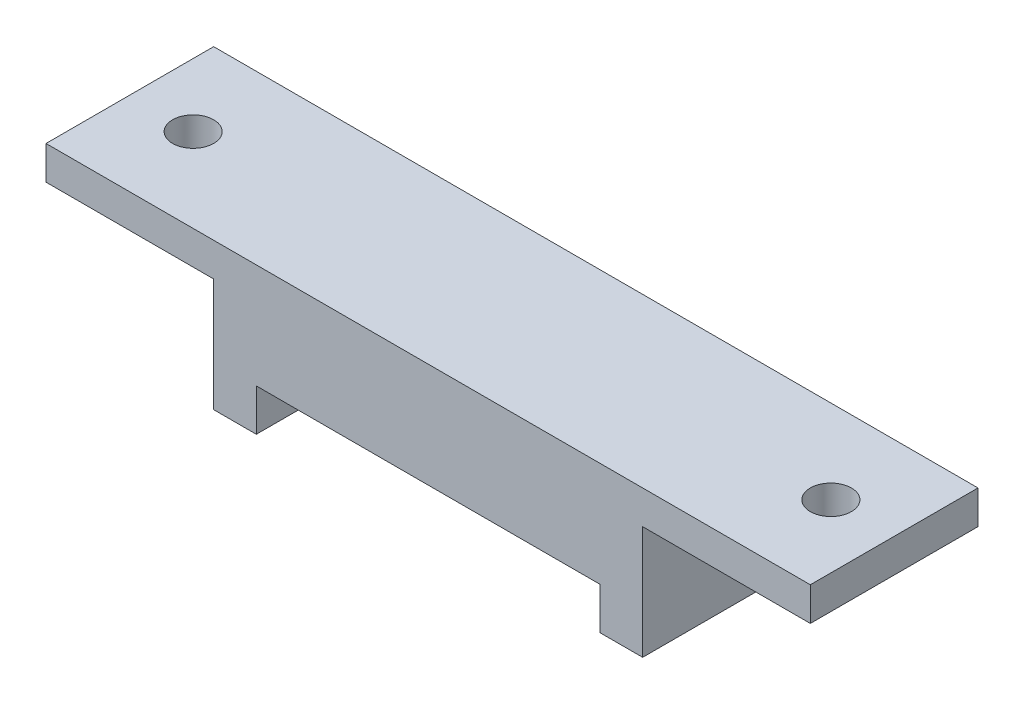
SolidWorks part; units mm, degrees
other "Markup1"
sketch "Sketch137" plane through (-51.679, 39.1617, 59.3908) normal (0, 0, 1) x (1, 0, 0)
material "PLA"
ref_plane "Front Plane" through (0, 0, 0) normal (0, 0, 1) x (1, 0, 0)
ref_plane "Top Plane" through (0, 0, 0) normal (0, 1, 0) x (1, 0, 0)
ref_plane "Right Plane" through (0, 0, 0) normal (1, 0, 0) x (0, 0, -1)
ref_plane "Plane1" through (45.486, 0, 0) normal (1, 0, 0) x (0, 0, -1)
sketch "Sketch1" plane through (45.486, 0, 0) normal (1, 0, 0) x (0, 0, -1)
  line L0 (-101.9708, 193.4267) -> (-101.9708, -38.8733)
  line L1 (-101.9708, -38.8733) -> (63.6092, -38.8733)
  line L2 (63.6092, -38.8733) -> (63.6092, 193.4267)
  line L3 (63.6092, 193.4267) -> (-101.9708, 193.4267)
extrude "Boss-Extrude1" add sketch "Sketch1" against normal blind 92.73
sketch "Sketch2" plane through (-47.244, 0, 0) normal (-1, 0, 0) x (0, 0, 1)
  line L0 (101.9708, 95.1267) -> (26.8208, 95.1267)
  line L1 (26.8208, 95.1267) -> (26.8208, -38.8733)
  line L2 (26.8208, -38.8733) -> (101.9708, -38.8733)
  line L3 (101.9708, -38.8733) -> (101.9708, 95.1267)
extrude "Cut-Extrude1" cut sketch "Sketch2" against normal through all
sketch "Sketch3" plane through (0, 0, 26.8208) normal (0, 0, 1) x (1, 0, 0)
  line L0 (-47.244, -38.8733) -> (-47.244, 54.6267)
  line L1 (-47.244, 54.6267) -> (45.486, 54.6267)
  line L2 (45.486, 54.6267) -> (45.486, -38.8733)
  line L3 (45.486, -38.8733) -> (-47.244, -38.8733)
extrude "Boss-Extrude2" add sketch "Sketch3" along normal blind 32.57
sketch "Sketch4" plane through (0, 0, 59.3908) normal (0, 0, 1) x (1, 0, 0)
  line L0 (1.0789, -38.8733) -> (1.0789, -28.8733)
  line L1 (2.0478, -28.2099) -> (5.3831, -22.8733)
  line L2 (5.3831, -22.8733) -> (9.856, -22.8733)
  line L3 (9.856, -22.8733) -> (9.856, 44.6267)
  line L4 (9.856, 44.6267) -> (-22.144, 44.6267)
  line L5 (-22.144, 44.6267) -> (-22.144, -22.8733)
  line L6 (-22.144, -22.8733) -> (-17.6711, -22.8733)
  line L7 (-17.6711, -22.8733) -> (-14.3054, -28.2585)
  line L8 (-13.3536, -28.8733) -> (-13.3536, -38.8733)
  line L9 (-13.3536, -38.8733) -> (1.0789, -38.8733)
  arc A0 (1.0789, -28.8733) -> (2.0478, -28.2099) centre (1.2316, -28.0571) ccw
  arc A1 (-14.3054, -28.2585) -> (-13.3536, -28.8733) centre (-13.5221, -28.0901) ccw
extrude "Cut-Extrude2" cut sketch "Sketch4" against normal blind 79.2
sketch "Sketch5" plane through (0, 0, -19.8092) normal (0, 0, 1) x (1, 0, 0)
  line L0 (9.856, -22.8733) -> (9.856, 44.6267)
  line L1 (9.856, 44.6267) -> (-22.144, 44.6267)
  line L2 (-22.144, 44.6267) -> (-22.144, -22.8733)
  line L3 (-22.144, -22.8733) -> (-17.6711, -22.8733)
  line L4 (-17.6711, -22.8733) -> (-14.3054, -28.2585)
  line L5 (-13.3536, -28.8733) -> (1.0789, -28.8733)
  line L6 (2.0478, -28.2099) -> (5.3831, -22.8733)
  line L7 (5.3831, -22.8733) -> (9.856, -22.8733)
  arc A0 (-14.3054, -28.2585) -> (-13.3536, -28.8733) centre (-13.5221, -28.0901) ccw
  arc A1 (1.0789, -28.8733) -> (2.0478, -28.2099) centre (1.2316, -28.0571) ccw
extrude "Cut-Extrude3" cut sketch "Sketch5" against normal blind 36.3
ref_plane "Plane2" through (14.356, 0, 0) normal (1, 0, 0) x (0, 0, -1)
sketch "Sketch6" plane through (14.356, 0, 0) normal (1, 0, 0) x (0, 0, -1)
  line L0 (-59.3908, 44.6267) -> (-59.3908, -6.8733)
  line L1 (-59.3908, -6.8733) -> (56.1092, -6.8733)
  line L2 (56.1092, -6.8733) -> (56.1092, 44.6267)
  line L3 (56.1092, 44.6267) -> (-59.3908, 44.6267)
extrude "Cut-Extrude4" cut sketch "Sketch6" against normal up to next
sketch "Sketch7" plane through (0, 0, 59.3908) normal (0, 0, 1) x (1, 0, 0)
  line L0 (14.356, 36.6267) -> (14.356, -6.8733)
  line L1 (14.356, -6.8733) -> (20.856, -6.8733)
  line L2 (24.956, -3.8733) -> (24.956, 34.1267)
  line L3 (24.956, 34.1267) -> (18.356, 34.1267)
  arc A0 (20.856, -6.8733) -> (24.956, -3.8733) centre (21.406, -3.3233) ccw
  arc A1 (18.356, 34.1267) -> (14.356, 36.6267) centre (17.606, 37.3767) cw
extrude "Cut-Extrude5" cut sketch "Sketch7" against normal blind 115.5
sketch "Sketch8" plane through (9.856, 0, 0) normal (-1, 0, 0) x (0, 0, 1)
  line L0 (59.3908, -17.3733) -> (59.3908, -6.8733)
  line L1 (59.3908, -6.8733) -> (-56.1092, -6.8733)
  line L2 (-56.1092, -6.8733) -> (-56.1092, -17.3733)
  line L3 (-56.1092, -17.3733) -> (59.3908, -17.3733)
extrude "Cut-Extrude6" cut sketch "Sketch8" against normal blind 4.5
ref_plane "Plane3" through (-35.644, 0, 0) normal (1, 0, 0) x (0, 0, -1)
sketch "Sketch9" plane through (-35.644, 0, 0) normal (1, 0, 0) x (0, 0, -1)
  line L0 (-59.3908, 44.6267) -> (56.1092, 44.6267)
  line L1 (56.1092, 44.6267) -> (56.1092, -13.3733)
  line L2 (56.1092, -13.3733) -> (-59.3908, -13.3733)
  line L3 (-59.3908, -13.3733) -> (-59.3908, 44.6267)
extrude "Cut-Extrude7" cut sketch "Sketch9" against normal blind 4.5 from surface starting at face at (-22.144, 10.8767, 1.6408)
sketch "Sketch10" plane through (0, 0, 59.3908) normal (0, 0, 1) x (1, 0, 0)
  line L0 (-26.644, -9.3733) -> (-26.644, 34.1267)
  line L1 (-26.644, 34.1267) -> (-37.144, 34.1267)
  line L2 (-37.144, 34.1267) -> (-37.144, -6.8733)
  line L3 (-37.144, -6.8733) -> (-30.644, -6.8733)
  arc A0 (-30.644, -6.8733) -> (-26.644, -9.3733) centre (-29.894, -10.1233) cw
extrude "Cut-Extrude8" cut sketch "Sketch10" against normal blind 115.5
sketch "Sketch11" plane through (0, 193.4267, 0) normal (0, 1, 0) x (-1, 0, 0)
  line L0 (38.664, 31.8208) -> (38.664, 96.9708)
  line L1 (38.664, 96.9708) -> (-40.486, 96.9708)
  line L2 (-40.486, 96.9708) -> (-40.486, 31.8208)
  line L3 (-40.486, 31.8208) -> (38.664, 31.8208)
extrude "Cut-Extrude9" cut sketch "Sketch11" against normal blind 90.3
sketch "Sketch12" plane through (40.486, 0, 0) normal (-1, 0, 0) x (0, 0, 1)
  line L0 (72.0692, 193.4267) -> (55.6292, 193.4267)
  line L1 (55.6292, 193.4267) -> (55.6292, 105.1267)
  line L2 (55.6292, 105.1267) -> (72.0692, 105.1267)
  line L3 (72.0692, 105.1267) -> (72.0692, 193.4267)
extrude "Cut-Extrude10" cut sketch "Sketch12" against normal through all
sketch "Sketch13" plane through (0, 103.1267, 0) normal (0, 1, 0) x (-1, 0, 0)
  line L0 (-22.986, 35.3208) -> (35.164, 35.3208)
  line L1 (35.164, 35.3208) -> (35.164, 93.4708)
  line L2 (35.164, 93.4708) -> (-22.986, 93.4708)
  line L3 (-22.986, 93.4708) -> (-22.986, 35.3208)
extrude "Cut-Extrude11" cut sketch "Sketch13" against normal blind 5
hole_wizard "Ø5.0 (5) Diameter Hole1" positions "Sketch15" profile "Sketch14" hole size "Ø5.0" standard "ANSI Metric"
sketch "Sketch15" plane through (0, 0, 59.3908) normal (0, 0, 1) x (1, 0, 0)
  point P0 (18.856, -11.3733)
  point P1 (-31.144, 38.6267)
  point P2 (18.856, 38.6267)
  point P3 (-31.144, -11.3733)
sketch "Sketch14" plane through (18.856, -11.3733, 59.3908) normal (1, 0, 0) x (0, -1, 0)
  line L0 (0, 0) -> (0, 5)
  line L1 (0, 5) -> (2.5, 5)
  line L2 (2.5, 5) -> (2.5, 0)
  line L5 (2.5, 0) -> (0, 0)
  line L10 (0, 5) -> (-2.5, 5) construction
  line L11 (0, -6.35) -> (0, 107.95) construction
  dimension "Hole Dia." = 5
  dimension "Hole Depth" = 5
  dimension "Drill Angle" = 180
hole_wizard "Ø4.9 (4.9) Diameter Hole1" positions "Sketch17" profile "Sketch16" hole size "Ø4.9" standard "ANSI Metric"
sketch "Sketch17" plane through (0, 95.1267, 0) normal (0, -1, 0) x (-1, 0, 0)
  point P0 (29.654, -87.9608)
  point P1 (-17.476, -40.8308)
  point P2 (-17.476, -87.9608)
  point P3 (29.654, -40.8308)
sketch "Sketch16" plane through (-29.654, 95.1267, 87.9608) normal (1, 0, 0) x (0, 0, -1)
  line L0 (0, 0) -> (0, 98.3)
  line L1 (0, 98.3) -> (2.45, 98.3)
  line L2 (2.45, 98.3) -> (2.45, 0)
  line L5 (2.45, 0) -> (0, 0)
  line L11 (0, -6.35) -> (0, 107.95) construction
  dimension "Thru Hole Dia." = 4.9
  dimension "Thru Hole Depth" = 98.3
hole_wizard "M36 Clearance Hole1" positions "Sketch19" profile "Sketch18" hole size "M36" standard "ANSI Metric"
sketch "Sketch19" plane through (0, 95.1267, 0) normal (0, -1, 0) x (-1, 0, 0)
  point P0 (6.089, -64.3958)
sketch "Sketch18" plane through (-6.089, 95.1267, 64.3958) normal (1, 0, 0) x (0, 0, -1)
  line L0 (0, 0) -> (0, 98.3)
  line L1 (0, 98.3) -> (19.55, 98.3)
  line L2 (19.55, 98.3) -> (19.55, 0)
  line L5 (19.55, 0) -> (0, 0)
  line L11 (0, -6.35) -> (0, 107.95) construction
  dimension "Thru Hole Dia." = 39.1
  dimension "Thru Hole Depth" = 98.3
hole_wizard "M45 Clearance Hole1" positions "Sketch21" profile "Sketch20" hole size "M45" standard "ANSI Metric"
sketch "Sketch21" plane through (0, 0, -56.1092) normal (0, 0, 1) x (1, 0, 0)
  point P0 (-6.144, 13.6267)
sketch "Sketch20" plane through (-6.144, 13.6267, -56.1092) normal (1, 0, 0) x (0, -1, 0)
  line L0 (0, 0) -> (0, 2.5)
  line L1 (0, 2.5) -> (24.87, 2.5)
  line L2 (24.87, 2.5) -> (24.87, 0)
  line L5 (24.87, 0) -> (0, 0)
  line L10 (0, 2.5) -> (-24.87, 2.5) construction
  line L11 (0, -6.35) -> (0, 107.95) construction
  dimension "Hole Dia." = 49.74
  dimension "Hole Depth" = 2.5
  dimension "Drill Angle" = 180
fillet "Fillet1" radius 2.5 6 edges at (14.356, -6.8733, 1.6408) (22.986, 100.6267, 35.3208) (-26.644, 34.1267, 1.6408) (22.986, 100.6267, 93.4708) (-35.164, 100.6267, 35.3208) (-35.164, 100.6267, 93.4708) tangent propagation no
fillet "Fillet2" radius 3.7583 2 edges at (-37.144, 34.1267, 1.6408) (14.356, 44.6267, 1.6408) tangent propagation no
sketch "Sketch22" plane through (-47.244, 0, 0) normal (-1, 0, 0) x (0, 0, 1)
  line L0 (59.3908, 54.6267) -> (59.3908, -38.8733) construction
  line L1 (-63.6092, -38.8733) -> (59.3908, -38.8733)
  line L2 (-63.6092, -38.8733) -> (-63.6092, -28.8733)
  line L3 (-63.6092, -28.8733) -> (59.3908, -28.8733)
  line L4 (59.3908, -38.8733) -> (59.3908, -28.8733)
  dimension "D1" = 10
extrude "Boss-Extrude3" add sketch "Sketch22" along normal blind 18
sketch "Sketch23" plane through (45.486, 0, 0) normal (1, 0, 0) x (0, 0, -1)
  line L0 (63.6092, -38.8733) -> (63.6092, 193.4267) construction
  line L1 (-59.3908, -38.8733) -> (63.6092, -38.8733)
  line L2 (-59.3908, -38.8733) -> (-59.3908, -28.8733)
  line L3 (-59.3908, -28.8733) -> (63.6092, -28.8733)
  line L4 (63.6092, -38.8733) -> (63.6092, -28.8733)
  dimension "D1" = 10
extrude "Boss-Extrude4" add sketch "Sketch23" along normal blind 17
fillet "Fillet3" radius 10 1 edges at (62.486, -33.8733, -63.6092)
sketch "Sketch24" plane through (0, -38.8733, 0) normal (0, -1, 0) x (1, 0, 0)
  line L0 (-65.244, 59.3908) -> (-13.3536, 59.3908) construction
  line L1 (-6.134, 137.3908) -> (-6.134, 27.3908) construction
  line L3 (1.0789, 59.3908) -> (62.486, 59.3908) construction
  line L4 (103.866, 27.3908) -> (-6.134, 27.3908) construction
  line L5 (45.486, -63.6092) -> (45.486, 59.3908) construction
  line L6 (45.486, -63.6092) -> (45.486, 59.3908)
  circle A0 centre (-6.134, 27.3908) radius 110
  point P0 (-6.134, 137.3908)
  point P4 (103.866, 27.3908)
  dimension "D1" = 78
  dimension "D2" = 51.62
  dimension "D3" = 32
  dimension "D4" = 58.38
sketch "Sketch25" plane through (0, -38.8733, 0) normal (0, -1, 0) x (1, 0, 0)
  circle A0 centre (-6.134, 27.3908) radius 91
  dimension "D1" = 182
sketch "Sketch26" plane through (0, -38.8733, 0) normal (0, -1, 0) x (1, 0, 0)
  line L0 (-65.244, -63.6092) -> (-65.244, 59.3908) construction
  line L1 (-65.244, -63.6092) -> (52.486, -63.6092) construction
  line L2 (-6.134, 13.742) -> (-6.134, -10.2463) construction
  line L3 (62.486, 59.3908) -> (62.486, -53.6092) construction
  line L4 (-65.244, 59.3908) -> (-47.244, 59.3908) construction
  line L5 (-56.244, 59.3908) -> (-56.244, -95.0248) construction
  line L6 (45.486, 59.3908) -> (62.486, 59.3908) construction
  line L7 (53.986, 59.3908) -> (53.986, -98.0271) construction
  circle A0 centre (-57.794, -56.1592) radius 3.95
  circle A2 centre (53.036, -54.1592) radius 3.95
  circle A3 centre (-56.244, 51.9408) radius 3.95
  circle A4 centre (-56.244, -2.1092) radius 3.95
  circle A5 centre (53.986, 51.9408) radius 3.95
  circle A6 centre (53.986, -2.1092) radius 3.95
  dimension "D1" = 7.9
  dimension "D4" = 7.9
  dimension "D9" = 7.9
  dimension "D10" = 7.9
  dimension "D11" = 7.9
  dimension "D12" = 7.9
  dimension "D2" = 7.45
  dimension "D3" = 7.45
  dimension "D5" = 9.45
  dimension "D6" = 9.45
  dimension "D7" = 61.5
  dimension "D8" = 7.45
extrude "Cut-Extrude12" cut sketch "Sketch26" against normal blind 17 contours A2 | A4 | A3 | A5 | A6 | A0 region at (53.036, -38.8733, -54.1592) region at (-56.244, -38.8733, 51.9408) region at (-56.244, -38.8733, -2.1092) region at (53.986, -38.8733, 51.9408) region at (53.986, -38.8733, -2.1092)
sketch "Sketch27" plane through (-47.244, 0, 0) normal (-1, 0, 0) x (0, 0, 1)
  line L0 (-63.6092, 54.6267) -> (77.7984, 54.6267) construction
  line L1 (-53.6092, 55.1367) -> (-53.6092, 74.5167)
  line L2 (-53.0992, 54.6267) -> (-33.7192, 54.6267)
  line L3 (-33.2092, 55.1367) -> (-33.2092, 74.5167)
  line L4 (-53.0992, 75.0267) -> (-33.7192, 75.0267)
  line L5 (-63.6092, -28.8733) -> (-63.6092, 193.4267) construction
  line L7 (-41.8509, 54.6267) -> (-41.8509, 57.7888) construction
  line L12 (26.8208, 54.6267) -> (-63.6092, 54.6267) construction
  line L14 (-41.8509, 54.6267) -> (-39.4339, 54.6267) construction
  arc A4 (-53.6092, 74.5167) -> (-53.0992, 75.0267) centre (-53.0992, 74.5167) cw
  arc A5 (-33.2092, 74.5167) -> (-33.7192, 75.0267) centre (-33.7192, 74.5167) ccw
  arc A6 (-53.6092, 55.1367) -> (-53.0992, 54.6267) centre (-53.0992, 55.1367) ccw
  arc A7 (-33.2092, 55.1367) -> (-33.7192, 54.6267) centre (-33.7192, 55.1367) cw
  point P6 (-41.8509, 54.6267)
  point P11 (-51.3509, 23.6267)
  point P12 (-51.8509, 23.1267)
  dimension "D4" = 0.51
  dimension "D5" = 0.51
  dimension "D7" = 0.51
  dimension "D8" = 0.51
  dimension "D10" = 27.4075
  dimension "D12" = 27.4075
  dimension "D15" = 0.51
  dimension "D2" = 20.4
  dimension "D3" = 20.4
  dimension "D6" = 10
  dimension "D9" = 0
  dimension "D11" = 19.38
  dimension "D13" = 28.138
  dimension "D14" = 19.89
extrude "Cut-Extrude14" cut sketch "Sketch27" against normal up to surface (92.73 mm away) contours L4 A5 L3 A7 L2 A6 L1 A4 up to face at (45.486, 102.1433, 42.0453)
sketch "Sketch28" plane through (-47.244, 0, 0) normal (-1, 0, 0) x (0, 0, 1)
  line L0 (-53.0992, 54.6267) -> (-33.7192, 54.6267) construction
  line L1 (-53.4092, 54.6267) -> (-33.4092, 54.6267)
  line L2 (-53.4092, 54.6267) -> (-53.4092, 24.6267)
  line L3 (-53.4092, 24.6267) -> (-33.4092, 24.6267)
  line L4 (-33.4092, 54.6267) -> (-33.4092, 24.6267)
  line L6 (-33.2092, 55.1367) -> (-33.2092, 74.5167) construction
  dimension "D1" = 30
  dimension "D2" = 20
  dimension "D3" = 0.2
extrude "Boss-Extrude5" add sketch "Sketch28" along normal blind 20
sketch "Sketch29" plane through (45.486, 0, 0) normal (1, 0, 0) x (0, 0, -1)
  line L0 (53.0992, 54.6267) -> (33.7192, 54.6267) construction
  line L1 (33.4092, 54.6267) -> (53.4092, 54.6267)
  line L2 (33.4092, 54.6267) -> (33.4092, 24.6267)
  line L3 (33.4092, 24.6267) -> (53.4092, 24.6267)
  line L4 (53.4092, 54.6267) -> (53.4092, 24.6267)
  line L5 (53.6092, 55.1367) -> (53.6092, 74.5167) construction
  dimension "D1" = 30
  dimension "D2" = 20
  dimension "D3" = 0.2
extrude "Boss-Extrude6" add sketch "Sketch29" along normal blind 20
sketch "Sketch30" plane through (-47.244, 0, 0) normal (-1, 0, 0) x (0, 0, 1)
  line L0 (-33.2092, 55.1367) -> (-33.2092, 74.5167) construction
  line L2 (0.7908, 59.3267) -> (-33.2092, 59.3267)
  line L3 (0.7908, 59.3267) -> (0.7908, 70.3267)
  line L4 (0.7908, 70.3267) -> (-33.2092, 70.3267)
  line L5 (-33.2092, 59.3267) -> (-33.2092, 70.3267)
  line L6 (0.7908, 59.3267) -> (-33.2092, 70.3267) construction
  line L7 (0.7908, 70.3267) -> (-33.2092, 59.3267) construction
  point P0 (-16.2092, 64.8267)
  point P3 (-16.2092, 64.8267)
  dimension "D1" = 17
  dimension "D2" = 11
extrude "Cut-Extrude15" cut sketch "Sketch30" against normal blind 4
sketch "Sketch31" plane through (-47.244, 0, 0) normal (-1, 0, 0) x (0, 0, 1)
  line L0 (-53.0992, 75.0267) -> (-33.7192, 75.0267) construction
  line L1 (-33.2092, 55.1367) -> (-33.2092, 59.3267) construction
  line L2 (-33.2092, 70.3267) -> (-33.2092, 59.3267) construction
  circle A2 centre (-28.2492, 64.8267) radius 2.45
  circle A3 centre (-8.2492, 64.8267) radius 2.45
  point P8 (-43.4092, 75.0267)
  point P13 (-33.2092, 64.8267)
  dimension "D5" = 4.9
  dimension "D6" = 4.9
  dimension "D7" = 4.96
  dimension "D8" = 20
extrude "Cut-Extrude16" cut sketch "Sketch31" against normal blind 11
sketch "Sketch32" plane through (-47.244, 0, 0) normal (-1, 0, 0) x (0, 0, 1)
  line L0 (-53.0992, 75.0267) -> (-33.7192, 75.0267) construction
  line L1 (-53.4092, 75.0267) -> (-33.4092, 75.0267)
  line L2 (-53.4092, 75.0267) -> (-53.4092, 105.0267)
  line L3 (-53.4092, 105.0267) -> (-33.4092, 105.0267)
  line L4 (-33.4092, 75.0267) -> (-33.4092, 105.0267)
  line L5 (-33.2092, 70.3267) -> (-33.2092, 74.5167) construction
  dimension "D1" = 30
  dimension "D2" = 20
  dimension "D3" = 0.2
extrude "Boss-Extrude7" add sketch "Sketch32" along normal blind 20
sketch "Sketch33" plane through (45.486, 0, 0) normal (1, 0, 0) x (0, 0, -1)
  line L0 (53.0992, 75.0267) -> (33.7192, 75.0267) construction
  line L1 (33.4092, 75.0267) -> (53.4092, 75.0267)
  line L2 (33.4092, 75.0267) -> (33.4092, 105.0267)
  line L3 (33.4092, 105.0267) -> (53.4092, 105.0267)
  line L4 (53.4092, 75.0267) -> (53.4092, 105.0267)
  line L5 (33.2092, 55.1367) -> (33.2092, 74.5167) construction
  dimension "D1" = 20
  dimension "D2" = 30
  dimension "D3" = 0.2
extrude "Boss-Extrude8" add sketch "Sketch33" along normal blind 20
sketch "Sketch34" plane through (-67.244, 0, 0) normal (-1, 0, 0) x (0, 0, 1)
  line L0 (-53.4092, 75.0267) -> (-33.4092, 75.0267) construction
  circle A0 centre (-43.4092, 79.9867) radius 2.45
  circle A1 centre (-43.4092, 99.9867) radius 2.45
  dimension "D1" = 4.9
  dimension "D2" = 4.9
  dimension "D3" = 4.96
  dimension "D4" = 20
extrude "Cut-Extrude17" cut sketch "Sketch34" against normal blind 11
sketch "Sketch36" plane through (-67.244, 0, 0) normal (-1, 0, 0) x (0, 0, 1)
  line L0 (-33.4092, 105.0267) -> (-53.4092, 105.0267) construction
  line L1 (-48.9092, 75.0267) -> (-37.9092, 75.0267)
  line L2 (-48.9092, 75.0267) -> (-48.9092, 105.0267)
  line L3 (-48.9092, 105.0267) -> (-37.9092, 105.0267)
  line L4 (-37.9092, 75.0267) -> (-37.9092, 105.0267)
  line L5 (-48.9092, 75.0267) -> (-37.9092, 105.0267) construction
  line L6 (-48.9092, 105.0267) -> (-37.9092, 75.0267) construction
  point P0 (-43.4092, 90.0267)
  point P1 (-43.4092, 90.0267)
  point P8 (-43.4092, 75.0267)
  dimension "D1" = 11
extrude "Cut-Extrude19" cut sketch "Sketch36" against normal blind 4
sketch "Sketch37" plane through (65.486, 0, 0) normal (1, 0, 0) x (0, 0, -1)
  line L0 (53.4092, 105.0267) -> (33.4092, 105.0267) construction
  line L1 (37.9092, 75.0267) -> (48.9092, 75.0267)
  line L2 (37.9092, 75.0267) -> (37.9092, 105.0267)
  line L3 (37.9092, 105.0267) -> (48.9092, 105.0267)
  line L4 (48.9092, 75.0267) -> (48.9092, 105.0267)
  line L5 (37.9092, 75.0267) -> (48.9092, 105.0267) construction
  line L6 (37.9092, 105.0267) -> (48.9092, 75.0267) construction
  point P0 (43.4092, 90.0267)
  point P2 (43.4092, 90.0267)
  dimension "D1" = 11
extrude "Cut-Extrude20" cut sketch "Sketch37" against normal blind 4
sketch "Sketch35" plane through (65.486, 0, 0) normal (1, 0, 0) x (0, 0, -1)
  line L0 (33.4092, 75.0267) -> (37.9092, 75.0267) construction
  circle A0 centre (43.4092, 79.9867) radius 2.45
  circle A1 centre (43.4092, 99.9867) radius 2.45
  dimension "D1" = 4.9
  dimension "D2" = 4.9
  dimension "D3" = 4.96
  dimension "D4" = 20
extrude "Cut-Extrude18" cut sketch "Sketch35" against normal blind 11
sketch "Sketch38" plane through (-67.244, 0, 0) normal (-1, 0, 0) x (0, 0, 1)
  line L0 (-33.4092, 54.6267) -> (-53.4092, 54.6267) construction
  line L1 (-53.4092, 54.6267) -> (-53.4092, 24.6267) construction
  line L3 (-48.9092, 24.6267) -> (-37.9092, 24.6267)
  line L4 (-48.9092, 24.6267) -> (-48.9092, 54.6267)
  line L5 (-48.9092, 54.6267) -> (-37.9092, 54.6267)
  line L6 (-37.9092, 24.6267) -> (-37.9092, 54.6267)
  line L7 (-48.9092, 24.6267) -> (-37.9092, 54.6267) construction
  line L8 (-48.9092, 54.6267) -> (-37.9092, 24.6267) construction
  point P0 (-43.4092, 39.6267)
  point P1 (-53.4092, 39.6267)
  point P2 (-43.4092, 54.6267)
  point P9 (-43.4092, 39.6267)
  dimension "D1" = 11
extrude "Cut-Extrude21" cut sketch "Sketch38" against normal blind 1.4
sketch "Sketch39" plane through (-65.844, 0, 0) normal (-1, 0, 0) x (0, 0, 1)
  line L0 (-37.9092, 54.6267) -> (-48.9092, 54.6267) construction
  circle A0 centre (-43.4092, 49.8667) radius 2.45
  circle A1 centre (-43.4092, 29.8667) radius 2.45
  point P4 (-43.4092, 54.6267)
  dimension "D1" = 4.9
  dimension "D2" = 4.9
  dimension "D3" = 24.76
  dimension "D4" = 4.76
extrude "Cut-Extrude22" cut sketch "Sketch39" against normal blind 7
sketch "Sketch40" plane through (-47.244, 0, 0) normal (-1, 0, 0) x (0, 0, 1)
  line L5 (-33.2092, 70.3267) -> (0.7908, 70.3267)
  line L6 (-33.2092, 70.3267) -> (-33.2092, 75.0267)
  line L7 (-33.2092, 75.0267) -> (0.7908, 75.0267)
  line L8 (0.7908, 70.3267) -> (0.7908, 75.0267)
  line L9 (-33.2092, 59.3267) -> (0.7908, 59.3267)
  line L10 (-33.2092, 59.3267) -> (-33.2092, 54.6267)
  line L11 (-33.2092, 54.6267) -> (0.7908, 54.6267)
  line L12 (0.7908, 59.3267) -> (0.7908, 54.6267)
extrude "Boss-Extrude10" add sketch "Sketch40" along normal blind 3.3
sketch "Sketch41" plane through (0, 0, -33.4092) normal (0, 0, 1) x (1, 0, 0)
  line L0 (-67.244, 75.0267) -> (-67.244, 105.0267) construction
  line L2 (-67.244, 105.0267) -> (-47.244, 105.0267) construction
  circle A0 centre (-60.644, 86.2767) radius 2.45
  point P0 (-60.644, 86.2767)
  dimension "D3" = 4.9
  dimension "D1" = 6.6
  dimension "D2" = 18.75
extrude "Cut-Extrude23" cut sketch "Sketch41" against normal blind 23.3
sketch "Sketch42" plane through (0, 0, -33.4092) normal (0, 0, 1) x (1, 0, 0)
  line L0 (-67.244, 75.0267) -> (-47.244, 75.0267) construction
  line L1 (-63.144, 75.0267) -> (-58.144, 75.0267)
  line L2 (-63.144, 75.0267) -> (-63.144, 95.5267)
  line L3 (-63.144, 95.5267) -> (-58.144, 95.5267)
  line L4 (-58.144, 75.0267) -> (-58.144, 95.5267)
  point P6 (-60.644, 75.0267)
  point P8 (-60.644, 95.5267)
  point P10 (-60.644, 86.2767)
  dimension "D1" = 5
  dimension "D2" = 20.5
extrude "Cut-Extrude24" cut sketch "Sketch42" against normal blind 1.2
sketch "Sketch43" plane through (0, 0, -53.4092) normal (0, 0, -1) x (-1, 0, 0)
  line L1 (65.5515, 86.2767) -> (63.0977, 90.5267)
  line L2 (63.0977, 90.5267) -> (58.1902, 90.5267)
  line L3 (58.1902, 90.5267) -> (55.7365, 86.2767)
  line L4 (55.7365, 86.2767) -> (58.1902, 82.0267)
  line L5 (58.1902, 82.0267) -> (63.0977, 82.0267)
  line L6 (63.0977, 82.0267) -> (65.5515, 86.2767)
  circle A0 centre (60.644, 86.2767) radius 4.25 construction
  dimension "D1" = 8.5
extrude "Cut-Extrude25" cut sketch "Sketch43" against normal blind 3
sketch "Sketch44" plane through (-47.244, 0, 0) normal (-1, 0, 0) x (0, 0, 1)
  line L4 (26.8208, 95.1267) -> (26.8208, 54.6267) construction
  line L5 (26.8208, 75.0267) -> (6.8208, 75.0267)
  line L6 (26.8208, 75.0267) -> (26.8208, 54.6267)
  line L7 (26.8208, 54.6267) -> (6.8208, 54.6267)
  line L8 (6.8208, 75.0267) -> (6.8208, 54.6267)
  point P0 (12.4474, 75.0267)
  dimension "D1" = 20
sketch "Sketch45" plane through (-47.244, 0, 0) normal (-1, 0, 0) x (0, 0, 1)
  line L5 (59.3908, 54.6267) -> (39.3908, 54.6267)
  line L6 (59.3908, 54.6267) -> (59.3908, 34.6267)
  line L7 (59.3908, 34.6267) -> (39.3908, 34.6267)
  line L8 (39.3908, 54.6267) -> (39.3908, 34.6267)
  dimension "D2" = 20
  dimension "D3" = 20
extrude "Boss-Extrude13" add sketch "Sketch45" along normal blind 4.7
sketch "Sketch46" plane through (-47.244, 0, 0) normal (-1, 0, 0) x (0, 0, 1)
  line L1 (39.3908, 54.6267) -> (19.3908, 54.6267)
  line L2 (39.3908, 54.6267) -> (39.3908, 34.6267)
  line L3 (39.3908, 34.6267) -> (19.3908, 34.6267)
  line L4 (19.3908, 54.6267) -> (19.3908, 34.6267)
  dimension "D1" = 20
extrude "Boss-Extrude14" add sketch "Sketch46" along normal blind 24
sketch "Sketch47" plane through (0, 0, 39.3908) normal (0, 0, 1) x (1, 0, 0)
  line L0 (-71.244, 34.6267) -> (-71.244, 54.6267) construction
  line L1 (-71.244, 54.6267) -> (-51.944, 54.6267) construction
  line L2 (-63.144, 34.6267) -> (-58.144, 34.6267)
  line L3 (-63.144, 34.6267) -> (-63.144, 54.6267)
  line L4 (-63.144, 54.6267) -> (-58.144, 54.6267)
  line L5 (-58.144, 34.6267) -> (-58.144, 54.6267)
  line L6 (-63.144, 34.6267) -> (-58.144, 54.6267) construction
  line L7 (-63.144, 54.6267) -> (-58.144, 34.6267) construction
  point P0 (-60.644, 44.6267)
  point P4 (-71.244, 44.6267)
  point P5 (-60.644, 44.6267)
  dimension "D1" = 10.6
  dimension "D2" = 5
extrude "Cut-Extrude26" cut sketch "Sketch47" against normal blind 1.2
sketch "Sketch48" plane through (0, 0, 38.1908) normal (0, 0, 1) x (1, 0, 0)
  line L0 (-71.244, 34.6267) -> (-71.244, 54.6267) construction
  line L1 (-71.244, 34.6267) -> (-63.144, 34.6267) construction
  circle A0 centre (-60.644, 43.9267) radius 2.45
  point P6 (-60.644, 41.4767)
  dimension "D1" = 4.9
  dimension "D2" = 10.6
  dimension "D3" = 9.3
extrude "Cut-Extrude27" cut sketch "Sketch48" against normal blind 31.2
sketch "Sketch49" plane through (0, 0, 19.3908) normal (0, 0, -1) x (-1, 0, 0)
  line L0 (67.244, 54.6267) -> (67.244, 24.6267) construction
  line L1 (64.894, 41.4729) -> (64.894, 46.3804)
  line L2 (64.894, 46.3804) -> (60.644, 48.8341)
  line L3 (60.644, 48.8341) -> (56.394, 46.3804)
  line L4 (56.394, 46.3804) -> (56.394, 41.4729)
  line L5 (56.394, 41.4729) -> (60.644, 39.0192)
  line L6 (60.644, 39.0192) -> (64.894, 41.4729)
  circle A0 centre (60.644, 43.9267) radius 4.25 construction
  dimension "D1" = 8.5
extrude "Cut-Extrude28" cut sketch "Sketch49" against normal blind 3
sketch "Sketch50" plane through (-71.244, 0, 0) normal (-1, 0, 0) x (0, 0, 1)
  line L0 (19.3908, 34.6267) -> (59.3908, 34.6267) construction
  line L1 (19.3908, 54.6267) -> (39.3908, 54.6267)
  line L2 (19.3908, 54.6267) -> (19.3908, 34.6267)
  line L3 (19.3908, 34.6267) -> (39.3908, 34.6267)
  line L4 (39.3908, 54.6267) -> (39.3908, 34.6267)
extrude "Cut-Extrude29" cut sketch "Sketch50" against normal blind 3
sketch "Sketch51" plane through (0, 193.4267, 0) normal (0, 1, 0) x (1, 0, 0)
  line L0 (-0.879, 63.6092) -> (-0.879, 22.3194) construction
  line L1 (-47.244, 63.6092) -> (45.486, 63.6092) construction
  line L2 (-0.879, 22.3194) -> (-0.879, 63.6092) construction
  line L3 (-0.879, 63.6092) -> (28.5075, 63.6092) construction
ref_plane "Plane5" through (-0.879, 0, 0) normal (-1, 0, 0) x (0, 0, 1)
mirror "Mirror1" about plane through (-0.879, 0, 0) normal (-1, 0, 0) of "Boss-Extrude10"
mirror "Mirror2" about plane through (-0.879, 0, 0) normal (-1, 0, 0) of "Cut-Extrude22", "Cut-Extrude21"
mirror "Mirror3" about plane through (-0.879, 0, 0) normal (-1, 0, 0) of "Cut-Extrude25", "Cut-Extrude23", "Cut-Extrude24"
mirror "Mirror4" about plane through (-0.879, 0, 0) normal (-1, 0, 0) of "Boss-Extrude14", "Cut-Extrude29", "Boss-Extrude13"
mirror "Mirror5" about plane through (-0.879, 0, 0) normal (-1, 0, 0) of "Cut-Extrude28", "Cut-Extrude27", "Cut-Extrude26"
sketch "Sketch52" plane through (0, 0, 101.9708) normal (0, 0, 1) x (1, 0, 0)
  line L0 (-47.244, 193.4267) -> (-47.244, 95.1267) construction
  line L1 (-6.094, 146.0315) -> (-6.094, 193.4267) construction
  line L2 (-47.244, 193.4267) -> (45.486, 193.4267) construction
  line L3 (-6.094, 146.0315) -> (-6.094, -38.8733) construction
  line L4 (-13.3536, -38.8733) -> (1.0789, -38.8733) construction
  line L5 (-0.879, 193.4267) -> (-0.879, -38.8733) construction
  line L6 (-0.879, 91.069) -> (-0.879, -91.069) construction
  line L8 (-15.879, 129.2767) -> (14.121, 129.2767)
  line L9 (-15.879, 129.2767) -> (-15.879, 159.2767)
  line L10 (-15.879, 159.2767) -> (14.121, 159.2767)
  line L11 (14.121, 129.2767) -> (14.121, 159.2767)
  line L12 (-15.879, 129.2767) -> (14.121, 159.2767) construction
  line L13 (-15.879, 159.2767) -> (14.121, 129.2767) construction
  point P1 (-6.094, 146.0315)
  point P15 (-0.879, 144.2767)
  point P20 (-47.244, 144.2767)
  dimension "D1" = 41.15
  dimension "D2" = 30
  dimension "D3" = 30
extrude "Boss-Extrude15" add sketch "Sketch52" along normal blind 50
sketch "Sketch53" plane through (-15.879, 0, 0) normal (-1, 0, 0) x (0, 0, 1)
  line L0 (101.9708, 95.1267) -> (151.9708, 129.2767)
  line L1 (151.9708, 129.2767) -> (101.9708, 129.2767)
  line L2 (101.9708, 129.2767) -> (101.9708, 95.1267)
extrude "Boss-Extrude16" add sketch "Sketch53" against normal up to surface (30 mm away) up to face at (14.121, 144.2767, 126.9708)
sketch "Sketch54" plane through (0, 0, 151.9708) normal (0, 0, 1) x (1, 0, 0)
  line L0 (-0.879, 91.069) -> (-0.879, -91.069) construction
  line L1 (-10.704, 133.9844) -> (8.8922, 133.9844)
  line L2 (-11.079, 134.3068) -> (-11.079, 154.062)
  line L3 (-10.704, 154.3844) -> (8.8922, 154.3844)
  line L4 (9.321, 134.3956) -> (9.321, 153.9732)
  line L5 (-11.079, 133.9844) -> (9.321, 154.3844) construction
  line L6 (-11.079, 154.3844) -> (9.321, 133.9844) construction
  line L7 (-0.879, 144.1844) -> (1.8975, 144.1844) construction
  arc A0 (-11.079, 154.062) -> (-10.704, 154.3844) centre (-10.6007, 153.885) cw
  arc A1 (8.8922, 154.3844) -> (9.321, 153.9732) centre (8.8197, 153.8796) cw
  arc A2 (8.8922, 133.9844) -> (9.321, 134.3956) centre (8.8197, 134.4892) ccw
  arc A3 (-11.079, 134.3068) -> (-10.704, 133.9844) centre (-10.6007, 134.4838) ccw
  point P0 (-0.879, 144.1844)
  dimension "D3" = 0.51
  dimension "D4" = 0.51
  dimension "D1" = 20.4
  dimension "D2" = 20.4
extrude "Cut-Extrude30" cut sketch "Sketch54" against normal blind 50
sketch "Sketch55" plane through (0, 159.2767, 0) normal (0, 1, 0) x (1, 0, 0)
  line L0 (-15.879, -151.9708) -> (-15.879, -101.9708) construction
  line L1 (-15.879, -142.9708) -> (14.121, -142.9708)
  line L2 (-15.879, -142.9708) -> (-15.879, -151.9708)
  line L3 (-15.879, -151.9708) -> (14.121, -151.9708)
  line L4 (14.121, -142.9708) -> (14.121, -151.9708)
  dimension "9" = 9
extrude "Boss-Extrude17" add sketch "Sketch55" along normal blind 18
sketch "Sketch56" plane through (0, 0, 151.9708) normal (0, 0, 1) x (1, 0, 0)
  line L0 (14.121, 159.2767) -> (-15.879, 159.2767) construction
  line L1 (14.121, 159.2767) -> (-15.879, 159.2767)
  line L2 (-15.879, 177.2767) -> (14.121, 177.2767) construction
  line L3 (-3.379, 159.2767) -> (1.621, 159.2767)
  line L4 (-3.379, 159.2767) -> (-3.379, 177.2767)
  line L5 (-3.379, 177.2767) -> (1.621, 177.2767)
  line L6 (1.621, 159.2767) -> (1.621, 177.2767)
  point P8 (-0.879, 159.2767)
  point P9 (-0.879, 177.2767)
  line M11 (14.121, 177.2767) -> (-15.879, 177.2767)
  dimension "D1" = 5
extrude "Cut-Extrude31" cut sketch "Sketch56" against normal blind 1.5 contours L1 L6 L4 M11 region at (-0.879, 168.2767, 151.9708)
sketch "Sketch57" plane through (0, 0, 150.4708) normal (0, 0, 1) x (1, 0, 0)
  line L0 (-0.879, 91.069) -> (-0.879, -91.069) construction
  line L1 (1.621, 159.2767) -> (-3.379, 159.2767) construction
  line L2 (-15.879, 177.2767) -> (-3.379, 177.2767) construction
  circle A0 centre (-0.879, 165.6367) radius 2.45
  point P5 (-0.879, 159.2767)
  dimension "D1" = 4.9
  dimension "D2" = 11.64
extrude "Cut-Extrude32" cut sketch "Sketch57" against normal blind 11.5
sketch "Sketch58" plane through (0, 0, 142.9708) normal (0, 0, -1) x (-1, 0, 0)
  line L1 (5.0318, 168.2515) -> (0.6909, 170.5405)
  line L2 (0.6909, 170.5405) -> (-3.4619, 167.9257)
  line L3 (-3.4619, 167.9257) -> (-3.2738, 163.0218)
  line L4 (-3.2738, 163.0218) -> (1.0671, 160.7328)
  line L5 (1.0671, 160.7328) -> (5.2199, 163.3476)
  line L6 (5.2199, 163.3476) -> (5.0318, 168.2515)
  circle A0 centre (0.879, 165.6367) radius 4.25 construction
  dimension "D1" = 8.5
extrude "Cut-Extrude33" cut sketch "Sketch58" against normal blind 3
sketch "Sketch59" plane through (-15.879, 0, 0) normal (-1, 0, 0) x (0, 0, 1)
  line L1 (151.9708, 129.2767) -> (142.9708, 129.2767)
  line L2 (151.9708, 129.2767) -> (151.9708, 159.2767)
  line L3 (151.9708, 159.2767) -> (142.9708, 159.2767)
  line L4 (142.9708, 129.2767) -> (142.9708, 159.2767)
extrude "Boss-Extrude18" add sketch "Sketch59" along normal blind 18
mirror "Mirror6" about plane through (-0.879, 0, 0) normal (-1, 0, 0) of "Boss-Extrude18"
sketch "Sketch61" plane through (-15.879, 0, 0) normal (-1, 0, 0) x (0, 0, 1)
  line L7 (142.9708, 146.6292) -> (142.9708, 159.2767)
  line L8 (142.9708, 159.2767) -> (101.9708, 159.2767)
  line L9 (101.9708, 159.2767) -> (101.9708, 95.1267)
  line L10 (101.9708, 95.1267) -> (151.9708, 129.2767)
  line L11 (151.9708, 129.2767) -> (142.9708, 129.2767)
  line L12 (142.9708, 129.2767) -> (142.9708, 141.7396)
  line L13 (142.9708, 141.7396) -> (142.9708, 146.6292)
  line L14 (142.9708, 146.6292) -> (142.9708, 159.2767)
  line L15 (142.9708, 159.2767) -> (101.9708, 159.2767)
  line L16 (101.9708, 159.2767) -> (101.9708, 95.1267)
  line L17 (101.9708, 95.1267) -> (151.9708, 129.2767)
  line L18 (151.9708, 129.2767) -> (142.9708, 129.2767)
  line L19 (142.9708, 129.2767) -> (142.9708, 141.7396)
  line L20 (142.9708, 141.7396) -> (142.9708, 146.6292)
  dimension "D1" = 0
sketch "Sketch62" plane through (0, 0, 151.9708) normal (0, 0, 1) x (1, 0, 0)
  line L0 (-11.079, 154.062) -> (-11.079, 134.3068) construction
  line L1 (-11.079, 141.6844) -> (-33.879, 141.6844)
  line L2 (-11.079, 141.6844) -> (-11.079, 146.6844)
  line L3 (-11.079, 146.6844) -> (-33.879, 146.6844)
  line L4 (-33.879, 141.6844) -> (-33.879, 146.6844)
  line L5 (-33.879, 129.2767) -> (-33.879, 159.2767) construction
  point P8 (-11.079, 144.1844)
  point P9 (-33.879, 144.1844)
  dimension "D1" = 5
extrude "Cut-Extrude35" cut sketch "Sketch62" against normal blind 1.5
sketch "Sketch63" plane through (0, 0, 150.4708) normal (0, 0, 1) x (1, 0, 0)
  line L0 (-33.879, 129.2767) -> (-33.879, 141.6844) construction
  line L3 (-11.079, 154.062) -> (-11.079, 134.3068) construction
  circle A0 centre (-22.329, 144.1844) radius 2.45
  point P7 (-11.079, 144.1844)
  dimension "D1" = 4.9
  dimension "D2" = 11.55
extrude "Cut-Extrude36" cut sketch "Sketch63" against normal blind 12
sketch "Sketch64" plane through (0, 0, 142.9708) normal (0, 0, -1) x (-1, 0, 0)
  line L1 (27.2365, 144.1844) -> (24.7827, 148.4344)
  line L2 (24.7827, 148.4344) -> (19.8752, 148.4344)
  line L3 (19.8752, 148.4344) -> (17.4215, 144.1844)
  line L4 (17.4215, 144.1844) -> (19.8752, 139.9344)
  line L5 (19.8752, 139.9344) -> (24.7827, 139.9344)
  line L6 (24.7827, 139.9344) -> (27.2365, 144.1844)
  circle A0 centre (22.329, 144.1844) radius 4.25 construction
  dimension "D1" = 8.5
extrude "Cut-Extrude37" cut sketch "Sketch64" against normal blind 3
mirror "Mirror7" about plane through (-0.879, 0, 0) normal (-1, 0, 0) of "Cut-Extrude37", "Cut-Extrude36", "Cut-Extrude35"
sketch "Sketch65" plane through (0, 159.2767, 0) normal (0, 1, 0) x (1, 0, 0)
  line L0 (14.121, -101.9708) -> (-15.879, -101.9708) construction
  line L1 (-11.379, -101.9708) -> (9.621, -101.9708)
  line L2 (-11.379, -101.9708) -> (-11.379, -142.9708)
  line L3 (-11.379, -142.9708) -> (9.621, -142.9708)
  line L4 (9.621, -101.9708) -> (9.621, -142.9708)
  line L5 (14.121, -142.9708) -> (-15.879, -142.9708) construction
  line L6 (-0.879, 59.565) -> (-0.879, -59.565) construction
  point P8 (-0.879, -101.9708)
  dimension "D1" = 21
sketch "Sketch67" plane through (0, 0, 151.9708) normal (0, 0, 1) x (1, 0, 0)
  line L0 (-15.879, 129.2767) -> (14.121, 129.2767) construction
  line L1 (-11.379, 129.2767) -> (9.621, 129.2767)
  line L2 (-11.379, 129.2767) -> (-11.379, 124.2767)
  line L3 (-11.379, 124.2767) -> (9.621, 124.2767)
  line L4 (9.621, 129.2767) -> (9.621, 124.2767)
  line L5 (-10.704, 133.9844) -> (8.8922, 133.9844) construction
  line L7 (-0.879, 59.565) -> (-0.879, -59.565) construction
  point P6 (-0.9059, 133.9844)
  point P7 (-0.879, 124.2767)
  dimension "D1" = 21
  dimension "D2" = 5
  dimension "D3" = 10.5
extrude "Cut-Extrude40" cut sketch "Sketch67" against normal blind 45
sketch "Sketch68" plane through (0, 133.9844, 0) normal (0, 1, 0) x (1, 0, 0)
  line L0 (-0.9059, -151.9708) -> (-0.9059, -101.9708) construction
  line L1 (-10.704, -151.9708) -> (8.8922, -151.9708) construction
  line L2 (-10.704, -101.9708) -> (8.8922, -101.9708) construction
  circle A0 centre (-0.9059, -137.4708) radius 2.45
  circle A1 centre (-0.9059, -117.4708) radius 2.45
  dimension "D1" = 4.9
  dimension "D2" = 4.9
  dimension "D3" = 14.5
  dimension "D4" = 20
sketch "Sketch69" plane through (0, 129.2767, 0) normal (0, -1, 0) x (1, 0, 0)
  circle A0 centre (-0.9059, 137.4708) radius 5
  circle A1 centre (-0.9059, 117.4708) radius 5
  dimension "D1" = 10
  dimension "D2" = 10
  dimension "D3" = 20
extrude "Cut-Extrude42" cut sketch "Sketch69" along normal blind 30
sketch "Sketch70" plane through (0, 0, -58.6092) normal (0, 0, 1) x (1, 0, 0)
  line L0 (-47.244, 34.6267) -> (-47.244, -28.8733) construction
  line L1 (50.186, 54.6267) -> (-51.944, 54.6267) construction
  line L2 (-6.094, 13.6267) -> (1.1155, 13.6267) construction
  point P0 (-6.094, 13.6267)
  dimension "D1" = 41.15
  dimension "D2" = 41
ref_plane "Plane6" through (0, 0, 64.3958) normal (0, 0, 1) x (1, 0, 0)
sketch "Sketch71" plane through (0, 0, 59.3908) normal (0, 0, 1) x (1, 0, 0)
  line L0 (-22.144, -13.3733) -> (-22.144, -22.8733) construction
  line L1 (-26.644, -13.3733) -> (-22.144, -13.3733)
  line L2 (-26.644, -13.3733) -> (-26.644, -17.3733)
  line L3 (-26.644, -17.3733) -> (-22.144, -17.3733)
  line L4 (-22.144, -13.3733) -> (-22.144, -17.3733)
extrude "Cut-Extrude43" cut sketch "Sketch71" against normal up to surface (115.5 mm away) up to face at (18.726, 13.6267, -56.1092)
sketch "Sketch72" plane through (0, 0, 59.3908) normal (0, 0, 1) x (1, 0, 0)
  line L0 (-22.144, -17.3733) -> (9.856, -17.3733)
  line L1 (-26.644, -17.3733) -> (-22.144, -17.3733)
  line L2 (9.616, -16.9083) -> (14.0485, -16.9083)
  line L3 (24.4895, -3.6108) -> (24.4895, 33.8192)
  line L4 (-28.799, 33.8192) -> (-32.977, 33.8192)
  line L5 (24.4895, 33.8192) -> (17.9885, 33.8192)
  line L6 (-36.679, -6.5658) -> (-30.2765, -6.5658)
  line L7 (16.511, -6.5658) -> (20.451, -6.5658)
  line L8 (10.3466, 44.1617) -> (-26.3365, 44.1617)
  line L9 (14.0485, 36.2817) -> (14.0485, 40.4597)
  line L10 (14.0485, -16.9083) -> (14.0485, -9.0283)
  line L11 (-26.3365, -16.9083) -> (-21.904, -16.9083)
  line L12 (-21.904, -16.9083) -> (9.616, -16.9083)
  line L13 (-26.3365, -9.0283) -> (-26.3365, -16.9083)
  line L14 (-26.3365, 44.1617) -> (-26.3365, 36.2817)
  line L15 (-36.679, 30.1172) -> (-36.679, -6.5658)
  line L20 (-26.644, -17.3733) -> (-22.144, -17.3733)
  line L21 (-22.144, -17.3733) -> (-22.144, -22.8733)
  line L22 (-22.144, -22.8733) -> (-17.6711, -22.8733)
  line L23 (-17.6711, -22.8733) -> (-14.3054, -28.2585)
  line L24 (-13.3536, -28.8733) -> (1.0789, -28.8733)
  line L25 (2.0478, -28.2099) -> (5.3831, -22.8733)
  line L26 (5.3831, -22.8733) -> (9.856, -22.8733)
  line L27 (9.856, -22.8733) -> (9.856, -17.3733)
  line L28 (9.856, -17.3733) -> (14.356, -17.3733)
  line L29 (14.356, -17.3733) -> (14.356, -9.3733)
  line L30 (16.856, -6.8733) -> (20.856, -6.8733)
  line L31 (24.956, -3.8733) -> (24.956, 34.1267)
  line L32 (24.956, 34.1267) -> (18.356, 34.1267)
  line L33 (14.356, 36.6267) -> (14.356, 40.8683)
  line L34 (10.5977, 44.6267) -> (-26.644, 44.6267)
  line L35 (-26.644, 44.6267) -> (-26.644, 36.6267)
  line L36 (-29.144, 34.1267) -> (-33.3857, 34.1267)
  line L37 (-37.144, 30.3683) -> (-37.144, -6.8733)
  line L38 (-37.144, -6.8733) -> (-30.644, -6.8733)
  line L39 (-26.644, -9.3733) -> (-26.644, -17.3733)
  line L48 (9.856, -17.3733) -> (14.356, -17.3733)
  line L49 (14.356, -17.3733) -> (14.356, -9.3733)
  line L50 (16.856, -6.8733) -> (20.856, -6.8733)
  line L51 (24.956, -3.8733) -> (24.956, 34.1267)
  line L52 (24.956, 34.1267) -> (18.356, 34.1267)
  line L53 (14.356, 36.6267) -> (14.356, 40.8683)
  line L54 (10.5977, 44.6267) -> (-26.644, 44.6267)
  line L55 (-26.644, 44.6267) -> (-26.644, 36.6267)
  line L56 (-29.144, 34.1267) -> (-33.3857, 34.1267)
  line L57 (-37.144, 30.3683) -> (-37.144, -6.8733)
  line L58 (-37.144, -6.8733) -> (-30.644, -6.8733)
  line L59 (-26.644, -9.3733) -> (-26.644, -17.3733)
  arc A0 (-32.977, 33.8192) -> (-36.679, 30.1172) centre (-32.977, 30.1172) ccw
  arc A1 (20.451, -6.5658) -> (24.4895, -3.6108) centre (20.9928, -3.0691) ccw
  arc A2 (16.511, -6.5658) -> (14.0485, -9.0283) centre (16.511, -9.0283) ccw
  arc A3 (-28.799, 33.8192) -> (-26.3365, 36.2817) centre (-28.799, 36.2817) ccw
  arc A4 (-26.3365, -9.0283) -> (-30.2765, -6.5658) centre (-29.5377, -9.7671) ccw
  arc A5 (14.0485, 40.4597) -> (10.3466, 44.1617) centre (10.3466, 40.4597) ccw
  arc A6 (14.0485, 36.2817) -> (17.9885, 33.8192) centre (17.2498, 37.0204) ccw
  arc A9 (-14.3054, -28.2585) -> (-13.3536, -28.8733) centre (-13.5221, -28.0901) ccw
  arc A10 (1.0789, -28.8733) -> (2.0478, -28.2099) centre (1.2316, -28.0571) ccw
  arc A11 (16.856, -6.8733) -> (14.356, -9.3733) centre (16.856, -9.3733) ccw
  arc A12 (20.856, -6.8733) -> (24.956, -3.8733) centre (21.406, -3.3233) ccw
  arc A13 (14.356, 36.6267) -> (18.356, 34.1267) centre (17.606, 37.3767) ccw
  arc A14 (14.356, 40.8683) -> (10.5977, 44.6267) centre (10.5977, 40.8683) ccw
  arc A15 (-29.144, 34.1267) -> (-26.644, 36.6267) centre (-29.144, 36.6267) ccw
  arc A16 (-33.3857, 34.1267) -> (-37.144, 30.3683) centre (-33.3857, 30.3683) ccw
  arc A17 (-26.644, -9.3733) -> (-30.644, -6.8733) centre (-29.894, -10.1233) ccw
  arc A20 (16.856, -6.8733) -> (14.356, -9.3733) centre (16.856, -9.3733) ccw
  arc A21 (20.856, -6.8733) -> (24.956, -3.8733) centre (21.406, -3.3233) ccw
  arc A22 (14.356, 36.6267) -> (18.356, 34.1267) centre (17.606, 37.3767) ccw
  arc A23 (14.356, 40.8683) -> (10.5977, 44.6267) centre (10.5977, 40.8683) ccw
  arc A24 (-29.144, 34.1267) -> (-26.644, 36.6267) centre (-29.144, 36.6267) ccw
  arc A25 (-33.3857, 34.1267) -> (-37.144, 30.3683) centre (-33.3857, 30.3683) ccw
  arc A26 (-26.644, -9.3733) -> (-30.644, -6.8733) centre (-29.894, -10.1233) ccw
  dimension "D1" = 0
extrude "Boss-Extrude19" add sketch "Sketch72" against normal up to surface (115.5 mm away) up to face at (-5.5448, 1.5602, -56.1092)
sketch "Sketch73" plane through (0, 0, 59.3908) normal (0, 0, 1) x (1, 0, 0)
  line L0 (14.0485, -16.9083) -> (-26.3365, -16.9083) construction
  line L1 (-22.144, -17.3733) -> (9.856, -17.3733)
  line L2 (-22.144, -17.3733) -> (-22.144, -16.9083)
  line L3 (-22.144, -16.9083) -> (9.856, -16.9083)
  line L4 (9.856, -17.3733) -> (9.856, -16.9083)
extrude "Cut-Extrude44" cut sketch "Sketch73" against normal up to surface (115.5 mm away) up to face at (18.726, 13.6267, -56.1092)
sketch "Sketch74" plane through (0, 0, 59.3908) normal (0, 0, 1) x (1, 0, 0)
  circle A0 centre (-31.144, 38.6267) radius 2.5
  circle A1 centre (18.856, 38.6267) radius 2.5
  circle A2 centre (-31.144, -11.3733) radius 2.5
  circle A3 centre (18.856, -11.3733) radius 2.5
extrude "Boss-Extrude21" add sketch "Sketch74" against normal up to surface (5 mm away) up to face at (-28.644, 38.6267, 54.3908)
sketch "Sketch75" plane through (0, 0, 59.3908) normal (0, 0, 1) x (1, 0, 0)
  line L0 (10.3466, 44.1617) -> (-26.3365, 44.1617) construction
  line L2 (-26.3365, 36.2817) -> (-26.3365, 44.1617) construction
  line L3 (-22.144, -16.9083) -> (-22.144, -22.8733) construction
  line L4 (-26.3365, -16.9083) -> (-22.144, -16.9083) construction
  line L5 (9.856, -22.8733) -> (9.856, -16.9083) construction
  line L6 (14.0485, -16.9083) -> (9.856, -16.9083) construction
  circle A0 centre (-31.0965, 38.0917) radius 2.45
  circle A1 centre (18.9066, 38.0917) radius 2.45
  circle A2 centre (-31.144, -11.9083) radius 2.45
  circle A3 centre (18.856, -11.9083) radius 2.45
  point P8 (10.3466, 44.1617)
  dimension "D3" = 4.9
  dimension "D4" = 4.9
  dimension "D7" = 4.9
  dimension "D10" = 4.9
  dimension "D1" = 6.07
  dimension "D2" = 4.76
  dimension "D5" = 8.56
  dimension "D6" = 6.07
  dimension "D8" = 9
  dimension "D9" = 5
  dimension "D11" = 9
  dimension "D12" = 5
extrude "Cut-Extrude45" cut sketch "Sketch75" against normal blind 5
sketch "Sketch76" plane through (-47.244, 0, 0) normal (-1, 0, 0) x (0, 0, 1)
  line L0 (1.3908, -28.8733) -> (1.3908, 193.4267) construction
  line L1 (59.3908, -28.8733) -> (-63.6092, -28.8733) construction
  line L2 (-63.6092, 193.4267) -> (101.9708, 193.4267) construction
  line L4 (59.3908, 34.6267) -> (59.3908, -28.8733) construction
  line L5 (64.3908, 193.4267) -> (64.3908, 95.1267) construction
  line L6 (101.9708, 95.1267) -> (26.8208, 95.1267) construction
  point P12 (32.8908, 139.4224)
  dimension "D1" = 58
  dimension "D2" = 5
  dimension "D3" = 31.5
sketch "Sketch77" plane through (0, 193.4267, 0) normal (0, 1, 0) x (1, 0, 0)
  line L0 (-6.089, -83.9458) -> (-6.089, 63.6092) construction
  line L1 (-47.244, 63.6092) -> (45.486, 63.6092) construction
  line L2 (-47.244, -32.8908) -> (45.486, -32.8908) construction
  line L3 (45.486, -55) -> (45.486, 55) construction
  circle A0 centre (-6.089, -64.3958) radius 19.55 construction
  circle A1 centre (-6.089, -32.8908) radius 38.7084
  point P7 (-47.244, -32.8908)
  point P15 (-6.089, -32.8908)
sketch "Sketch78" plane through (0, -38.8733, 0) normal (0, -1, 0) x (1, 0, 0)
  circle A0 centre (-6.089, 32.8908) radius 38.7084 construction
  circle A1 centre (-6.089, 32.8908) radius 38.7084
  point P3 (-6.089, 71.5992)
  point P4 (-44.7974, 32.8908)
  point P5 (-6.089, -5.8176)
  point P6 (32.6195, 32.8908)
sketch "Sketch79" plane through (-67.244, 0, 0) normal (-1, 0, 0) x (0, 0, 1)
  line L1 (-53.4092, 105.0267) -> (11.6734, 105.0267)
  line L2 (-53.4092, 105.0267) -> (-53.4092, 14.2859)
  line L3 (-53.4092, 14.2859) -> (11.6734, 14.2859)
  line L4 (11.6734, 105.0267) -> (11.6734, 14.2859)
extrude "Cut-Extrude46" cut sketch "Sketch79" against normal up to surface (20 mm away) up to face at (-47.244, 64.8267, -34.4456)
sketch "Sketch80" plane through (-36.244, 0, 0) normal (-1, 0, 0) x (0, 0, 1)
  line L1 (-33.2092, 70.3267) -> (0.7908, 70.3267)
  line L2 (-33.2092, 70.3267) -> (-33.2092, 59.3267)
  line L3 (-33.2092, 59.3267) -> (0.7908, 59.3267)
  line L4 (0.7908, 70.3267) -> (0.7908, 59.3267)
extrude "Boss-Extrude22" add sketch "Sketch80" along normal up to surface (11 mm away) up to face at (-47.244, 64.8267, -34.3425)
sketch "Sketch81" plane through (65.486, 0, 0) normal (1, 0, 0) x (0, 0, -1)
  line L1 (53.4092, 105.0267) -> (-10.5506, 105.0267)
  line L2 (53.4092, 105.0267) -> (53.4092, 24.6267)
  line L3 (53.4092, 24.6267) -> (-10.5506, 24.6267)
  line L4 (-10.5506, 105.0267) -> (-10.5506, 24.6267)
extrude "Cut-Extrude47" cut sketch "Sketch81" against normal up to surface (20 mm away) up to face at (45.486, 92.4981, 38.8089)
sketch "Sketch82" plane through (66.486, 0, 0) normal (1, 0, 0) x (0, 0, -1)
  line L1 (-19.3908, 54.6267) -> (-59.3908, 54.6267)
  line L2 (-19.3908, 54.6267) -> (-19.3908, 34.6267)
  line L3 (-19.3908, 34.6267) -> (-59.3908, 34.6267)
  line L4 (-59.3908, 54.6267) -> (-59.3908, 34.6267)
extrude "Cut-Extrude48" cut sketch "Sketch82" against normal up to surface (21 mm away) up to face at (45.486, 64.8267, -43.4092)
sketch "Sketch83" plane through (-68.244, 0, 0) normal (-1, 0, 0) x (0, 0, 1)
  line L1 (19.3908, 54.6267) -> (59.3908, 54.6267)
  line L2 (19.3908, 54.6267) -> (19.3908, 34.6267)
  line L3 (19.3908, 34.6267) -> (59.3908, 34.6267)
  line L4 (59.3908, 54.6267) -> (59.3908, 34.6267)
extrude "Cut-Extrude49" cut sketch "Sketch83" against normal up to surface (21 mm away) up to face at (-47.244, 64.8267, -43.4092)
sketch "Sketch84" plane through (45.486, 0, 0) normal (1, 0, 0) x (0, 0, -1)
  line L1 (32.6262, 54.1497) -> (54.1922, 54.1497)
  line L2 (32.6262, 54.1497) -> (32.6262, 75.5036)
  line L3 (32.6262, 75.5036) -> (54.1922, 75.5036)
  line L4 (54.1922, 54.1497) -> (54.1922, 75.5036)
  line L5 (32.6262, 54.1497) -> (54.1922, 75.5036) construction
  line L6 (32.6262, 75.5036) -> (54.1922, 54.1497) construction
  point P0 (43.4092, 64.8267)
extrude "Boss-Extrude23" add sketch "Sketch84" against normal up to surface (92.73 mm away) up to face at (-47.244, 78.5767, 31.1433)
sketch "Sketch85" plane through (-47.244, 0, 0) normal (-1, 0, 0) x (0, 0, 1)
  line L0 (-63.6092, -28.8733) -> (-63.6092, 193.4267) construction
  line L1 (26.8208, 54.6267) -> (-63.6092, 54.6267)
  line L2 (26.8208, 54.6267) -> (26.8208, 85.1267)
  line L3 (26.8208, 85.1267) -> (-63.6092, 85.1267)
  line L4 (-63.6092, 54.6267) -> (-63.6092, 85.1267)
  dimension "D1" = 30.5
extrude "Cut-Extrude50" cut sketch "Sketch85" against normal blind 9
sketch "Sketch86" plane through (45.486, 0, 0) normal (1, 0, 0) x (0, 0, -1)
  line L0 (63.6092, -28.8733) -> (63.6092, 193.4267) construction
  line L1 (-26.8208, 54.6267) -> (63.6092, 54.6267)
  line L2 (-26.8208, 54.6267) -> (-26.8208, 85.1267)
  line L3 (-26.8208, 85.1267) -> (63.6092, 85.1267)
  line L4 (63.6092, 54.6267) -> (63.6092, 85.1267)
  dimension "D1" = 30.5
extrude "Cut-Extrude51" cut sketch "Sketch86" against normal blind 9
sketch "Sketch87" plane through (0, 0, -63.6092) normal (0, 0, -1) x (-1, 0, 0)
  line L0 (-16.486, 54.6267) -> (-16.486, 85.1267) construction
  line L1 (-36.486, 54.6267) -> (-36.486, 85.1267) construction
  line L2 (18.244, 85.1267) -> (18.244, 54.6267) construction
  line L3 (38.244, 85.1267) -> (38.244, 54.6267) construction
  line L13 (-16.486, 85.1267) -> (18.244, 85.1267)
  line L14 (-16.486, 85.1267) -> (-16.486, 54.6267)
  line L15 (-16.486, 54.6267) -> (18.244, 54.6267)
  line L16 (18.244, 85.1267) -> (18.244, 54.6267)
  dimension "D1" = 20
  dimension "20" = 20
extrude "Cut-Extrude52" cut sketch "Sketch87" against normal up to surface (90.43 mm away) up to face at (-0.879, 80.0017, 26.8208)
sketch "Sketch88" plane through (0, 0, 151.9708) normal (0, 0, 1) x (1, 0, 0)
  line L0 (32.121, 159.2767) -> (14.121, 159.2767) construction
  line L1 (-15.879, 159.2767) -> (14.121, 159.2767)
  line L2 (-15.879, 159.2767) -> (-15.879, 177.2767)
  line L3 (-15.879, 177.2767) -> (14.121, 177.2767)
  line L4 (14.121, 159.2767) -> (14.121, 177.2767)
  line L5 (14.121, 129.2767) -> (32.121, 129.2767)
  line L6 (14.121, 129.2767) -> (14.121, 159.2767)
  line L7 (14.121, 159.2767) -> (32.121, 159.2767)
  line L8 (32.121, 129.2767) -> (32.121, 159.2767)
  line L10 (-33.879, 159.2767) -> (-15.879, 159.2767)
  line L11 (-33.879, 159.2767) -> (-33.879, 129.2767)
  line L12 (-33.879, 129.2767) -> (-15.879, 129.2767)
  line L13 (-15.879, 159.2767) -> (-15.879, 129.2767)
  line M1 (9.321, 146.6844) -> (32.121, 146.6844)
  line M2 (32.121, 146.6844) -> (32.121, 159.2767)
  line M3 (32.121, 159.2767) -> (14.121, 159.2767)
  line M4 (14.121, 159.2767) -> (14.121, 177.2767)
  line M5 (14.121, 177.2767) -> (1.621, 177.2767)
  line M6 (1.621, 177.2767) -> (1.621, 159.2767)
  line M7 (1.621, 159.2767) -> (-3.379, 159.2767)
  line M8 (-3.379, 159.2767) -> (-3.379, 177.2767)
  line M9 (-3.379, 177.2767) -> (-15.879, 177.2767)
  line M10 (-15.879, 177.2767) -> (-15.879, 159.2767)
  line M11 (-15.879, 159.2767) -> (-33.879, 159.2767)
  line M12 (-33.879, 159.2767) -> (-33.879, 146.6844)
  line M13 (-33.879, 146.6844) -> (-11.079, 146.6844)
extrude "Cut-Extrude53" cut sketch "Sketch88" against normal blind 9 contours L13 M11 M12 M13 | L13 L11 L12 M13 | L3 M8 M7 M6 | L1 M6 M4 M5 | L1 M10 M8 M9 | L6 M1 M2 M3 | L5 L8 L6 M1 region at (-9.629, 168.2767, 151.9708) region at (23.121, 152.9805, 151.9708) region at (-24.879, 152.9805, 151.9708) region at (-0.879, 168.2767, 151.9708) region at (-24.879, 137.9805, 151.9708) region at (7.871, 168.2767, 151.9708) region at (23.121, 137.9805, 151.9708)
sketch "Sketch89" plane through (-15.879, 0, 0) normal (-1, 0, 0) x (0, 0, 1)
  line L0 (151.9708, 129.2767) -> (101.9708, 129.2767)
  line L1 (101.9708, 193.4267) -> (101.9708, 95.1267) construction
  line L2 (101.9708, 129.2767) -> (101.9708, 95.1267)
  line L3 (101.9708, 95.1267) -> (151.9708, 129.2767)
extrude "Boss-Extrude24" add sketch "Sketch89" against normal up to surface (30 mm away) up to face at (14.121, 139.9618, 139.0958)
sketch "Sketch90" plane through (0, 0, 150.4708) normal (0, 0, 1) x (1, 0, 0)
  line L0 (-11.079, 154.062) -> (-11.079, 134.3068) construction
  line L1 (-15.879, 146.6844) -> (-11.079, 146.6844)
  line L2 (-15.879, 146.6844) -> (-15.879, 141.6844)
  line L3 (-15.879, 141.6844) -> (-11.079, 141.6844)
  line L4 (-11.079, 146.6844) -> (-11.079, 141.6844)
  line L5 (-11.079, 141.6844) -> (-11.079, 146.6844) construction
  line L7 (9.321, 146.6844) -> (14.121, 146.6844)
  line L8 (9.321, 146.6844) -> (9.321, 141.6844)
  line L9 (9.321, 141.6844) -> (14.121, 141.6844)
  line L10 (14.121, 146.6844) -> (14.121, 141.6844)
extrude "Boss-Extrude25" add sketch "Sketch90" along normal up to surface (1.5 mm away) up to face at (-0.8819, 152.2212, 151.9708)
sketch "Sketch91" plane through (0, 0, 101.9708) normal (0, 0, 1) x (1, 0, 0)
  line L0 (-10.704, 133.9844) -> (8.8922, 133.9844) construction
  line L1 (-11.079, 154.3844) -> (-5.129, 154.3844)
  line L2 (-11.079, 154.3844) -> (-11.079, 133.9844)
  line L3 (-11.079, 133.9844) -> (-5.129, 133.9844)
  line L4 (-5.129, 154.3844) -> (-5.129, 133.9844)
  line L5 (8.8922, 154.3844) -> (-10.704, 154.3844) construction
  line L6 (9.321, 133.9844) -> (3.371, 133.9844)
  line L7 (9.321, 133.9844) -> (9.321, 154.3844)
  line L8 (9.321, 154.3844) -> (3.371, 154.3844)
  line L9 (3.371, 133.9844) -> (3.371, 154.3844)
  line L10 (9.321, 134.3956) -> (9.321, 153.9732) construction
  dimension "D1" = 8.5
  dimension "D2" = 5.95
extrude "Boss-Extrude26" add sketch "Sketch91" along normal up to surface (50 mm away) up to face at (-0.879, 144.2767, 151.9708)
sketch "Sketch92" plane through (0, 0, 151.9708) normal (0, 0, 1) x (1, 0, 0)
  line L1 (-5.129, 154.3844) -> (-10.129, 154.3844)
  line L2 (-5.129, 154.3844) -> (-5.129, 144.9588)
  line L3 (-5.129, 144.9588) -> (-10.129, 144.9588)
  line L4 (-10.129, 154.3844) -> (-10.129, 144.9588)
  dimension "D1" = 5
  dimension "D2" = 9.4256
sketch "Sketch93" plane through (0, 0, 151.9708) normal (0, 0, 1) x (1, 0, 0)
  line L0 (-0.879, 59.565) -> (-0.879, -59.565) construction
  line L1 (-5.129, 128.4344) -> (3.371, 128.4344)
  line L2 (-5.129, 128.4344) -> (-5.129, 159.9344)
  line L3 (-5.129, 159.9344) -> (3.371, 159.9344)
  line L4 (3.371, 128.4344) -> (3.371, 159.9344)
  line L5 (-5.129, 128.4344) -> (3.371, 159.9344) construction
  line L6 (-5.129, 159.9344) -> (3.371, 128.4344) construction
  point P0 (-0.879, 144.1844)
  dimension "D1" = 31.5
sketch "Sketch94" plane through (0, 0, 151.9708) normal (0, 0, 1) x (1, 0, 0)
  line L0 (-5.129, 128.4344) -> (3.371, 159.9344) construction
  line L1 (-10.129, 123.4344) -> (8.371, 123.4344)
  line L2 (-10.129, 123.4344) -> (-10.129, 164.9344)
  line L3 (-10.129, 164.9344) -> (8.371, 164.9344)
  line L4 (8.371, 123.4344) -> (8.371, 164.9344)
  line L5 (-10.129, 123.4344) -> (8.371, 164.9344) construction
  line L6 (-10.129, 164.9344) -> (8.371, 123.4344) construction
  line L7 (3.371, 128.4344) -> (3.371, 159.9344) construction
  line L8 (-5.129, 159.9344) -> (3.371, 159.9344) construction
  point P0 (-0.879, 144.1844)
  line M8 (3.371, 154.3844) -> (3.371, 133.9844)
  line M9 (3.371, 133.9844) -> (-5.129, 133.9844)
  line M10 (-5.129, 133.9844) -> (-5.129, 154.3844)
  line M11 (-5.129, 154.3844) -> (3.371, 154.3844)
  line M12 (-15.879, 129.2767) -> (14.121, 129.2767)
  line M14 (14.121, 159.2767) -> (-15.879, 159.2767)
  dimension "D1" = 5
  dimension "D2" = 5
extrude "Boss-Extrude27" add sketch "Sketch94" against normal up to surface (50 mm away) contours L4 L3 L2 M14 | L4 L2 M12 M14 M11 M8 M9 M10 | L1 L4 L2 M12 region at (-0.879, 126.3555, 151.9708) region at (-9.7765, 144.2767, 151.9708) region at (-0.879, 162.1055, 151.9708) up to face at (-0.879, 135.7392, 101.9708)
sketch "Sketch95" plane through (0, 0, 151.9708) normal (0, 0, 1) x (1, 0, 0)
  line L0 (-5.129, 128.4344) -> (3.371, 159.9344) construction
  line L1 (-15.879, 129.0921) -> (14.121, 129.0921)
  line L2 (-15.879, 129.0921) -> (-15.879, 159.2767)
  line L3 (-15.879, 159.2767) -> (14.121, 159.2767)
  line L4 (14.121, 129.0921) -> (14.121, 159.2767)
  line L5 (-15.879, 129.0921) -> (14.121, 159.2767) construction
  line L6 (-15.879, 159.2767) -> (14.121, 129.0921) construction
  line L8 (-10.129, 129.0921) -> (8.371, 129.0921)
  line L9 (-10.129, 129.0921) -> (-10.129, 159.2767)
  line L10 (-10.129, 159.2767) -> (8.371, 159.2767)
  line L11 (8.371, 129.0921) -> (8.371, 159.2767)
  line L12 (-10.129, 129.0921) -> (8.371, 159.2767) construction
  line L13 (-10.129, 159.2767) -> (8.371, 129.0921) construction
  line L14 (-15.879, 129.0921) -> (14.121, 129.0921)
  line L15 (-15.879, 129.0921) -> (-15.879, 95.1267)
  line L16 (-15.879, 95.1267) -> (14.121, 95.1267)
  line L17 (14.121, 129.0921) -> (14.121, 95.1267)
  line L18 (-10.129, 129.0921) -> (-15.879, 129.0921)
  line L19 (-10.129, 129.0921) -> (-10.129, 95.1267)
  line L20 (-10.129, 95.1267) -> (-15.879, 95.1267)
  line L21 (-15.879, 129.0921) -> (-15.879, 95.1267)
  line L22 (8.371, 129.0921) -> (14.121, 129.0921)
  line L23 (8.371, 129.0921) -> (8.371, 95.1267)
  line L24 (8.371, 95.1267) -> (14.121, 95.1267)
  line L25 (14.121, 129.0921) -> (14.121, 95.1267)
  point P0 (-0.879, 144.1844)
  point P8 (-0.879, 144.1844)
  line M1 (14.121, 159.2767) -> (8.371, 159.2767)
  line M5 (-10.129, 159.2767) -> (-15.879, 159.2767)
  line M6 (-15.879, 159.2767) -> (-15.879, 129.2767)
  line M7 (-15.879, 129.2767) -> (-10.129, 129.2767)
  line M8 (-10.129, 129.2767) -> (-10.129, 123.4344)
  line M10 (8.371, 123.4344) -> (8.371, 129.2767)
  line M11 (8.371, 129.2767) -> (14.121, 129.2767)
  line M12 (14.121, 129.2767) -> (14.121, 159.2767)
extrude "Cut-Extrude54" cut sketch "Sketch95" against normal blind 50 and the other way through all contours L9 M7 M5 M6 | L11 M11 M12 M1 | L23 L16 L17 L1 M10 | L19 L1 L15 L16 M8 region at (-13.004, 112.1094, 151.9708) region at (-13.004, 144.2767, 151.9708) region at (11.246, 112.1094, 151.9708) region at (11.246, 144.2767, 151.9708)
sketch "Sketch96" plane through (0, 0, 151.9708) normal (0, 0, 1) x (1, 0, 0)
  line L0 (14.356, -91.069) -> (14.356, 91.069) construction
  line L1 (-10.129, 129.2767) -> (-16.5724, 129.2767)
  line L2 (-10.129, 129.2767) -> (-10.129, 128.4472)
  line L3 (-10.129, 128.4472) -> (-16.5724, 128.4472)
  line L4 (-16.5724, 129.2767) -> (-16.5724, 128.4472)
  line L5 (8.371, 129.2767) -> (14.356, 129.2767)
  line L6 (8.371, 129.2767) -> (8.371, 128.8619)
  line L7 (8.371, 128.8619) -> (14.356, 128.8619)
  line L8 (14.356, 129.2767) -> (14.356, 128.8619)
extrude "Cut-Extrude55" cut sketch "Sketch96" against normal blind 50
sketch "Sketch97" plane through (0, 0, 59.3908) normal (0, 0, 1) x (1, 0, 0)
  line L0 (-66.5722, 54.6267) -> (-66.5722, -28.8733) construction
  line L2 (-36.679, -6.5658) -> (-36.679, 30.1172) construction
  dimension "D1" = 29.8932
sketch "Sketch98" plane through (-38.244, 0, 0) normal (-1, 0, 0) x (0, 0, 1)
  line L0 (59.3908, 54.6267) -> (-63.6092, 54.6267) construction
  line L1 (-63.6092, 85.1267) -> (26.8208, 85.1267)
  line L2 (-63.6092, 85.1267) -> (-63.6092, 54.6267)
  line L3 (-63.6092, 54.6267) -> (26.8208, 54.6267)
  line L4 (26.8208, 85.1267) -> (26.8208, 54.6267)
  line L5 (-63.6092, 54.6267) -> (26.8208, 54.6267) construction
extrude "Boss-Extrude28" add sketch "Sketch98" along normal blind 13
sketch "Sketch99" plane through (-47.244, 0, 0) normal (-1, 0, 0) x (0, 0, 1)
  line L0 (-63.6092, 85.1267) -> (-63.6092, 193.4267) construction
  line L1 (26.8208, 85.1267) -> (-63.6092, 85.1267)
  line L2 (26.8208, 85.1267) -> (26.8208, 95.1267)
  line L3 (26.8208, 95.1267) -> (-63.6092, 95.1267)
  line L4 (-63.6092, 85.1267) -> (-63.6092, 95.1267)
  line L5 (-63.6092, -28.8733) -> (-63.6092, 54.6267) construction
  line L6 (26.8208, 54.6267) -> (-63.6092, 54.6267)
  line L7 (26.8208, 54.6267) -> (26.8208, 44.6267)
  line L8 (26.8208, 44.6267) -> (-63.6092, 44.6267)
  line L9 (-63.6092, 54.6267) -> (-63.6092, 44.6267)
  dimension "D1" = 10
  dimension "D2" = 10
extrude "Boss-Extrude29" add sketch "Sketch99" along normal blind 13
sketch "Sketch100" plane through (-47.244, 0, 0) normal (-1, 0, 0) x (0, 0, 1)
  line L1 (26.8208, 44.6267) -> (59.3908, 44.6267)
  line L2 (26.8208, 44.6267) -> (26.8208, 54.6267)
  line L3 (26.8208, 54.6267) -> (59.3908, 54.6267)
  line L4 (59.3908, 44.6267) -> (59.3908, 54.6267)
extrude "Boss-Extrude30" add sketch "Sketch100" along normal up to surface (13 mm away) up to face at (-60.244, 49.6267, -18.3942)
mirror "Mirror8" about plane through (-0.879, 0, 0) normal (-1, 0, 0) of "Boss-Extrude30", "Boss-Extrude29", "Boss-Extrude28"
sketch "Sketch102" plane through (0, 0, -63.6092) normal (0, 0, -1) x (-1, 0, 0)
  line L1 (-24.486, 54.6267) -> (26.244, 54.6267)
  line L2 (-24.486, 54.6267) -> (-24.486, 85.1267)
  line L3 (-24.486, 85.1267) -> (26.244, 85.1267)
  line L4 (26.244, 54.6267) -> (26.244, 85.1267)
  line L5 (-24.486, 54.6267) -> (26.244, 85.1267) construction
  line L6 (-24.486, 85.1267) -> (26.244, 54.6267) construction
  line L8 (51.244, 85.1267) -> (51.244, 54.6267) construction
  line L9 (-49.486, 85.1267) -> (-49.486, 54.6267) construction
  point P0 (0.879, 69.8767)
  dimension "D1" = 25
  dimension "D2" = 25
extrude "Cut-Extrude56" cut sketch "Sketch102" against normal blind 99
sketch "Sketch103" plane through (0, 0, 151.9708) normal (0, 0, 1) x (1, 0, 0)
  line L0 (-0.879, 54.065) -> (-0.879, -54.065) construction
  line L1 (-5.079, 159.3844) -> (3.321, 159.3844)
  line L2 (-5.079, 159.3844) -> (-5.079, 128.9844)
  line L3 (-5.079, 128.9844) -> (3.321, 128.9844)
  line L4 (3.321, 159.3844) -> (3.321, 128.9844)
  line L5 (-5.079, 159.3844) -> (3.321, 128.9844) construction
  line L6 (-5.079, 128.9844) -> (3.321, 159.3844) construction
  point P0 (-0.879, 144.1844)
  dimension "D1" = 8.4
  dimension "D2" = 30.4
extrude "Cut-Extrude57" cut sketch "Sketch103" against normal blind 50
sketch "Sketch104" plane through (0, 0, 101.9708) normal (0, 0, 1) x (1, 0, 0)
  line L1 (3.321, 154.3844) -> (3.371, 154.3844)
  line L2 (-5.079, 154.3844) -> (-5.129, 154.3844)
  line L3 (-5.079, 154.3844) -> (-5.079, 133.9844)
  line L4 (-5.079, 133.9844) -> (-5.129, 133.9844)
  line L5 (-5.129, 154.3844) -> (-5.129, 133.9844)
  line L6 (3.321, 154.3844) -> (3.321, 133.9844)
  line L7 (3.321, 133.9844) -> (3.371, 133.9844)
  line L8 (3.371, 154.3844) -> (3.371, 133.9844)
extrude "Boss-Extrude31" add sketch "Sketch104" along normal up to surface (50 mm away) up to face at (-0.879, 144.1844, 151.9708)
sketch "Sketch105" plane through (0, 0, -63.6092) normal (0, 0, -1) x (-1, 0, 0)
  line L0 (51.244, 85.1267) -> (51.244, 54.6267) construction
  line L1 (60.244, 85.1267) -> (51.244, 85.1267)
  line L2 (60.244, 85.1267) -> (60.244, 85.0767)
  line L3 (60.244, 85.0767) -> (51.244, 85.0767)
  line L4 (51.244, 85.1267) -> (51.244, 85.0767)
  line L6 (51.244, 54.6267) -> (60.244, 54.6267)
  line L7 (51.244, 54.6267) -> (51.244, 54.6767)
  line L8 (51.244, 54.6767) -> (60.244, 54.6767)
  line L9 (60.244, 54.6267) -> (60.244, 54.6767)
  dimension "D1" = 0.05
  dimension "D2" = 0.05
extrude "Boss-Extrude32" add sketch "Sketch105" against normal up to surface (90.43 mm away) up to face at (-0.879, 79.2695, 26.8208)
sketch "Sketch106" plane through (0, 0, 26.8208) normal (0, 0, 1) x (1, 0, 0)
  line L0 (58.486, 54.6267) -> (-60.244, 54.6267) construction
  line L1 (-60.244, 54.6767) -> (-51.244, 54.6767)
  line L2 (-60.244, 54.6767) -> (-60.244, 54.6267)
  line L3 (-60.244, 54.6267) -> (-51.244, 54.6267)
  line L4 (-51.244, 54.6767) -> (-51.244, 54.6267)
extrude "Boss-Extrude33" add sketch "Sketch106" along normal up to surface (32.57 mm away) up to face at (-28.6465, 38.0917, 59.3908)
mirror "Mirror9" about plane through (-0.879, 0, 0) normal (-1, 0, 0) of "Boss-Extrude33", "Boss-Extrude32"
sketch "Sketch109" plane through (0, 0, 151.9708) normal (0, 0, 1) x (1, 0, 0)
  line L1 (-10.129, 164.9344) -> (8.371, 164.9344)
  line L2 (-10.129, 164.9344) -> (-10.129, 123.4344)
  line L3 (-10.129, 123.4344) -> (8.371, 123.4344)
  line L4 (8.371, 164.9344) -> (8.371, 123.4344)
  line L5 (-5.079, 159.3844) -> (3.321, 159.3844)
  line L6 (-5.079, 159.3844) -> (-5.079, 128.9844)
  line L7 (-5.079, 128.9844) -> (3.321, 128.9844)
  line L8 (3.321, 159.3844) -> (3.321, 128.9844)
extrude "Boss-Extrude34" add sketch "Sketch109" along normal blind 20
sketch "Sketch110" plane through (0, 0, -63.6092) normal (0, 0, -1) x (-1, 0, 0)
  line L0 (-58.486, 95.1267) -> (-58.486, 85.0767)
  line L1 (-58.486, 85.0767) -> (-49.486, 85.0767)
  line L2 (-49.486, 85.0767) -> (-49.486, 54.6767)
  line L3 (-49.486, 54.6767) -> (-58.486, 54.6767)
  line L4 (-58.486, 54.6767) -> (-58.486, 44.6267)
  line L5 (-58.486, 44.6267) -> (60.244, 44.6267)
  line L6 (60.244, 44.6267) -> (60.244, 54.6767)
  line L7 (60.244, 54.6767) -> (51.244, 54.6767)
  line L8 (51.244, 54.6767) -> (51.244, 85.0767)
  line L9 (51.244, 85.0767) -> (60.244, 85.0767)
  line L10 (60.244, 85.0767) -> (60.244, 95.1267)
  line L11 (60.244, 95.1267) -> (-58.486, 95.1267)
  line L13 (-24.486, 85.1267) -> (26.244, 85.1267)
  line L14 (-24.486, 85.1267) -> (-24.486, 54.6267)
  line L15 (-24.486, 54.6267) -> (26.244, 54.6267)
  line L16 (26.244, 85.1267) -> (26.244, 54.6267)
extrude "Boss-Extrude35" add sketch "Sketch110" along normal blind 5
sketch "Sketch112" plane through (0, -38.8733, 0) normal (0, -1, 0) x (1, 0, 0)
  line L0 (-65.244, -63.6092) -> (52.486, -63.6092)
  line L1 (52.486, -63.6092) -> (59.5571, -60.6803)
  line L2 (59.5571, -60.6803) -> (-65.244, -60.6803) construction
  line L3 (-65.244, -63.6092) -> (-65.244, 59.3908) construction
  line L4 (-65.244, -63.6092) -> (-65.244, -64.6092)
  arc A1 (52.486, -63.6092) -> (62.486, -53.6092) centre (52.486, -53.6092) ccw construction
  arc A2 (59.5571, -60.6803) -> (-65.244, -64.6092) centre (-5.6932, 27.8771) cw
  dimension "D1" = 110
  dimension "D2" = 1
ref_plane "Plane7" through (0, 0, 32.8908) normal (0, 0, 1) x (1, 0, 0)
sketch "Sketch113" plane through (0, 193.4267, 0) normal (0, 1, 0) x (1, 0, 0)
  line L1 (-92.9425, 82.9544) -> (79.1122, 82.9544)
  line L2 (-92.9425, 82.9544) -> (-92.9425, -183.4327)
  line L3 (-92.9425, -183.4327) -> (79.1122, -183.4327)
  line L4 (79.1122, 82.9544) -> (79.1122, -183.4327)
extrude "Cut-Extrude58" cut sketch "Sketch113" against normal up to surface (138.8 mm away) up to face at (-0.879, 54.6267, 11.1058)
sketch "Sketch114" plane through (-65.244, 0, 0) normal (-1, 0, 0) x (0, 0, 1)
  line L1 (-88.4783, 64.7412) -> (89.9282, 64.7412)
  line L2 (-88.4783, 64.7412) -> (-88.4783, -59.1766)
  line L3 (-88.4783, -59.1766) -> (89.9282, -59.1766)
  line L4 (89.9282, 64.7412) -> (89.9282, -59.1766)
extrude "Cut-Extrude59" cut sketch "Sketch114" against normal up to surface (18 mm away) up to face at (-47.244, 7.8767, -2.1092)
sketch "Sketch115" plane through (62.486, 0, 0) normal (1, 0, 0) x (0, 0, -1)
  line L1 (-77.5463, 72.5244) -> (99.5282, 72.5244)
  line L2 (-77.5463, 72.5244) -> (-77.5463, -63.5481)
  line L3 (-77.5463, -63.5481) -> (99.5282, -63.5481)
  line L4 (99.5282, 72.5244) -> (99.5282, -63.5481)
extrude "Cut-Extrude60" cut sketch "Sketch115" against normal up to surface (17 mm away) up to face at (45.486, 7.8767, -2.1092)
sketch "Sketch116" plane through (0, 0, -68.6092) normal (0, 0, -1) x (-1, 0, 0)
  line L1 (-59.3633, 81.9775) -> (74.4193, 81.9775)
  line L2 (-59.3633, 81.9775) -> (-59.3633, -73.7438)
  line L3 (-59.3633, -73.7438) -> (74.4193, -73.7438)
  line L4 (74.4193, 81.9775) -> (74.4193, -73.7438)
extrude "Cut-Extrude61" cut sketch "Sketch116" against normal blind 108
sketch "Sketch117" plane through (0, 0, 59.3908) normal (0, 0, 1) x (1, 0, 0)
  line L0 (45.486, -38.8733) -> (45.486, 54.6267) construction
  line L1 (-47.244, 54.6267) -> (45.486, 54.6267)
  line L2 (-47.244, 54.6267) -> (-47.244, 49.1617)
  line L3 (-47.244, 49.1617) -> (45.486, 49.1617)
  line L4 (45.486, 54.6267) -> (45.486, 49.1617)
  line L5 (10.3466, 44.1617) -> (-26.3365, 44.1617) construction
  line L6 (-36.679, 30.1172) -> (-36.679, -6.5658) construction
  line L7 (-47.244, -38.8733) -> (-41.679, -38.8733)
  line L8 (-47.244, -38.8733) -> (-47.244, 49.1617)
  line L9 (-47.244, 49.1617) -> (-41.679, 49.1617)
  line L10 (-41.679, -38.8733) -> (-41.679, 49.1617)
  line L11 (24.4895, -3.6108) -> (24.4895, 33.8192) construction
  line L12 (45.486, -38.8733) -> (29.4895, -38.8733)
  line L13 (45.486, -38.8733) -> (45.486, 49.1617)
  line L14 (45.486, 49.1617) -> (29.4895, 49.1617)
  line L15 (29.4895, -38.8733) -> (29.4895, 49.1617)
  line M8 (45.486, -38.8733) -> (45.486, 54.6267)
  line M9 (45.486, 54.6267) -> (-47.244, 54.6267)
  line M10 (-47.244, 54.6267) -> (-47.244, -38.8733)
  line M11 (-47.244, -38.8733) -> (-13.3536, -38.8733)
  line M42 (1.0789, -38.8733) -> (45.486, -38.8733)
  dimension "D1" = 5
  dimension "D2" = 5
  dimension "D3" = 5
extrude "Cut-Extrude62" cut sketch "Sketch117" against normal blind 20 contours L3 M10 M8 M9 | L10 L3 M11 M10 | L15 L3 M42 M8 region at (-0.879, 51.8942, 59.3908) region at (-44.4615, 5.1442, 59.3908) region at (37.4878, 5.1442, 59.3908)
sketch "Sketch118" plane through (0, 0, 59.3908) normal (0, 0, 1) x (1, 0, 0)
  line L0 (29.4895, -38.8733) -> (29.4895, 49.1617) construction
  line L1 (-41.679, -38.8733) -> (29.4895, -38.8733)
  line L2 (-41.679, -38.8733) -> (-41.679, -33.8733)
  line L3 (-41.679, -33.8733) -> (29.4895, -33.8733)
  line L4 (29.4895, -38.8733) -> (29.4895, -33.8733)
  dimension "D1" = 5
extrude "Cut-Extrude63" cut sketch "Sketch118" against normal blind 20
sketch "Sketch119" plane through (0, 0, 54.3908) normal (0, 0, 1) x (1, 0, 0)
  circle A0 centre (-31.0965, 38.0917) radius 2.45
  circle A1 centre (18.9066, 38.0917) radius 2.45
  circle A2 centre (18.856, -11.9083) radius 2.45
  circle A3 centre (-31.144, -11.9083) radius 2.45
extrude "Boss-Extrude36" add sketch "Sketch119" along normal up to surface (5 mm away) up to face at (21.3566, 38.0917, 59.3908)
sketch "Sketch120" plane through (-13.3536, 0, 0) normal (1, 0, 0) x (0, 0, -1)
  line L1 (-59.3908, -33.8733) -> (-39.3908, -33.8733)
  line L2 (-59.3908, -33.8733) -> (-59.3908, -28.8733)
  line L3 (-59.3908, -28.8733) -> (-39.3908, -28.8733)
  line L4 (-39.3908, -33.8733) -> (-39.3908, -28.8733)
extrude "Boss-Extrude37" add sketch "Sketch120" along normal up to surface (14.4325 mm away) up to face at (1.0789, -31.3733, 49.3908)
sketch "Sketch121" plane through (0, 49.1617, 0) normal (0, 1, 0) x (1, 0, 0)
  line L4 (-41.679, -59.3908) -> (29.4895, -59.3908)
  line L5 (29.4895, -59.3908) -> (29.4895, -39.3908)
  line L6 (29.4895, -39.3908) -> (-41.679, -39.3908)
  line L7 (-41.679, -39.3908) -> (-41.679, -59.3908)
  line L8 (-41.679, -59.3908) -> (29.4895, -59.3908)
  line L9 (29.4895, -59.3908) -> (29.4895, -39.3908)
  line L10 (29.4895, -39.3908) -> (-41.679, -39.3908)
  line L11 (-41.679, -39.3908) -> (-41.679, -59.3908)
  dimension "D1" = 0
extrude "Boss-Extrude38" add sketch "Sketch121" along normal blind 7.5
sketch "Sketch123" plane through (29.4895, 0, 0) normal (1, 0, 0) x (0, 0, -1)
  line L0 (-39.3908, -33.8733) -> (-39.3908, 56.6617) construction
  line L1 (-59.3908, 56.6617) -> (-39.3908, 56.6617)
  line L2 (-59.3908, 56.6617) -> (-59.3908, 51.6617)
  line L3 (-59.3908, 51.6617) -> (-39.3908, 51.6617)
  line L4 (-39.3908, 56.6617) -> (-39.3908, 51.6617)
  dimension "D1" = 5
sketch "Sketch124" plane through (-41.679, 0, 0) normal (-1, 0, 0) x (0, 0, 1)
  line L0 (59.3908, -33.8733) -> (59.3908, 56.6617) construction
  line L1 (39.3908, 56.6617) -> (59.3908, 56.6617)
  line L2 (39.3908, 56.6617) -> (39.3908, 51.6617)
  line L3 (39.3908, 51.6617) -> (59.3908, 51.6617)
  line L4 (59.3908, 56.6617) -> (59.3908, 51.6617)
  dimension "D1" = 5
sketch "Sketch126" plane through (29.4895, 0, 0) normal (1, 0, 0) x (0, 0, -1)
  line L0 (-39.3908, -33.8733) -> (-39.3908, 56.6617) construction
  line L1 (-59.3908, 51.6617) -> (-39.3908, 51.6617)
  line L2 (-59.3908, 51.6617) -> (-59.3908, 37.6617)
  line L3 (-59.3908, 37.6617) -> (-39.3908, 37.6617)
  line L4 (-39.3908, 51.6617) -> (-39.3908, 37.6617)
  dimension "D1" = 14
extrude "Cut-Extrude65" cut sketch "Sketch126" against normal blind 10
extrude "Boss-Extrude41" add sketch "Sketch123" along normal blind 10
sketch "Sketch128" plane through (0, 51.6617, 0) normal (0, -1, 0) x (1, 0, 0)
  line L0 (29.4895, 39.3908) -> (29.4895, 59.3908) construction
  circle A0 centre (31.9395, 49.3908) radius 2.45
  point P0 (31.9395, 49.3908)
  dimension "D2" = 4.9
  dimension "D1" = 2.45
extrude "Cut-Extrude66" cut sketch "Sketch128" against normal blind 10
ref_plane "Plane8" through (-6.0955, 0, 0) normal (1, 0, 0) x (0, 0, -1)
mirror "Mirror10" about plane through (-6.0955, 0, 0) normal (1, 0, 0) of "Cut-Extrude65"
extrude "Boss-Extrude42" add sketch "Sketch124" along normal blind 10
sketch "Sketch129" plane through (0, 51.6617, 0) normal (0, -1, 0) x (1, 0, 0)
  line L0 (-41.679, 39.3908) -> (-41.679, 59.3908) construction
  circle A0 centre (-44.129, 49.3908) radius 2.45
  point P0 (-44.129, 49.3908)
  dimension "D2" = 4.9
  dimension "D1" = 2.45
extrude "Cut-Extrude67" cut sketch "Sketch129" against normal blind 10
sketch "Sketch130" plane through (0, 0, 39.3908) normal (0, 0, -1) x (-1, 0, 0)
  line L1 (-29.4895, -33.8733) -> (41.679, -33.8733)
  line L2 (-29.4895, -33.8733) -> (-29.4895, 37.6617)
  line L3 (-29.4895, 37.6617) -> (41.679, 37.6617)
  line L4 (41.679, -33.8733) -> (41.679, 37.6617)
extrude "Cut-Extrude68" cut sketch "Sketch130" against normal blind 20
sketch "Sketch131" plane through (0, 0, 59.3908) normal (0, 0, 1) x (1, 0, 0)
  line L0 (14.0485, 37.6617) -> (14.0485, 44.1617)
  line L1 (14.0485, 44.1617) -> (10.3466, 44.1617)
  line L2 (10.3466, 44.1617) -> (14.0485, 37.6617)
extrude "Cut-Extrude69" cut sketch "Sketch131" against normal blind 20
sketch "Sketch132" plane through (0, 37.6617, 0) normal (0, -1, 0) x (1, 0, 0)
  line L1 (-31.6805, 59.3908) -> (-26.3365, 59.3908)
  line L2 (-31.6805, 59.3908) -> (-31.6805, 39.3908)
  line L3 (-31.6805, 39.3908) -> (-26.3365, 39.3908)
  line L4 (-26.3365, 59.3908) -> (-26.3365, 39.3908)
  line L5 (19.4895, 59.3908) -> (14.0485, 59.3908)
  line L6 (19.4895, 59.3908) -> (19.4895, 39.3908)
  line L7 (19.4895, 39.3908) -> (14.0485, 39.3908)
  line L8 (14.0485, 59.3908) -> (14.0485, 39.3908)
extrude "Cut-Extrude70" cut sketch "Sketch132" against normal blind 1.5
sketch "Sketch133" plane through (0, 0, 39.3908) normal (0, 0, -1) x (-1, 0, 0)
  line L0 (-14.0485, 39.1617) -> (-19.4895, 39.1617) construction
  line L1 (-14.3535, 39.1617) -> (26.6415, 39.1617)
  line L2 (-14.3535, 39.1617) -> (-14.3535, 44.1617)
  line L3 (-14.3535, 44.1617) -> (26.6415, 44.1617)
  line L4 (26.6415, 39.1617) -> (26.6415, 44.1617)
  line L5 (-14.0485, 39.1617) -> (-14.0485, 44.1617) construction
  line L6 (26.3365, 44.1617) -> (26.3365, 39.1617) construction
  dimension "D1" = 0.305
  dimension "D2" = 0.305
extrude "Cut-Extrude71" cut sketch "Sketch133" against normal blind 20
sketch "Sketch134" plane through (0, 0, 59.3908) normal (0, 0, 1) x (1, 0, 0)
  line L0 (19.4895, 39.1617) -> (14.3535, 39.1617) construction
  line L1 (14.3535, 44.1617) -> (14.4035, 44.1617)
  line L2 (14.3535, 44.1617) -> (14.3535, 39.1617)
  line L3 (14.3535, 39.1617) -> (14.4035, 39.1617)
  line L4 (14.4035, 44.1617) -> (14.4035, 39.1617)
  dimension "D1" = 0.05
extrude "Cut-Extrude72" cut sketch "Sketch134" against normal blind 20
sketch "Sketch135" plane through (0, 0, 59.3908) normal (0, 0, 1) x (1, 0, 0)
  line L1 (-26.6415, 44.1617) -> (-26.5915, 44.1617)
  line L2 (-26.6415, 44.1617) -> (-26.6415, 39.1617)
  line L3 (-26.6415, 39.1617) -> (-26.5915, 39.1617)
  line L4 (-26.5915, 44.1617) -> (-26.5915, 39.1617)
  dimension "D1" = 0.05
extrude "Boss-Extrude43" add sketch "Sketch135" against normal blind 20
sketch "Sketch138" plane through (0, 51.6617, 0) normal (0, -1, 0) x (1, 0, 0)
  line L1 (-51.679, 59.3908) -> (-31.6805, 59.3908)
  line L2 (-51.679, 59.3908) -> (-51.679, 39.3908)
  line L3 (-51.679, 39.3908) -> (-31.6805, 39.3908)
  line L4 (-31.6805, 59.3908) -> (-31.6805, 39.3908)
  line L5 (19.4895, 39.3908) -> (39.4895, 39.3908)
  line L6 (19.4895, 39.3908) -> (19.4895, 59.3908)
  line L7 (19.4895, 59.3908) -> (39.4895, 59.3908)
  line L8 (39.4895, 39.3908) -> (39.4895, 59.3908)
extrude "Cut-Extrude73" cut sketch "Sketch138" against normal blind 1
